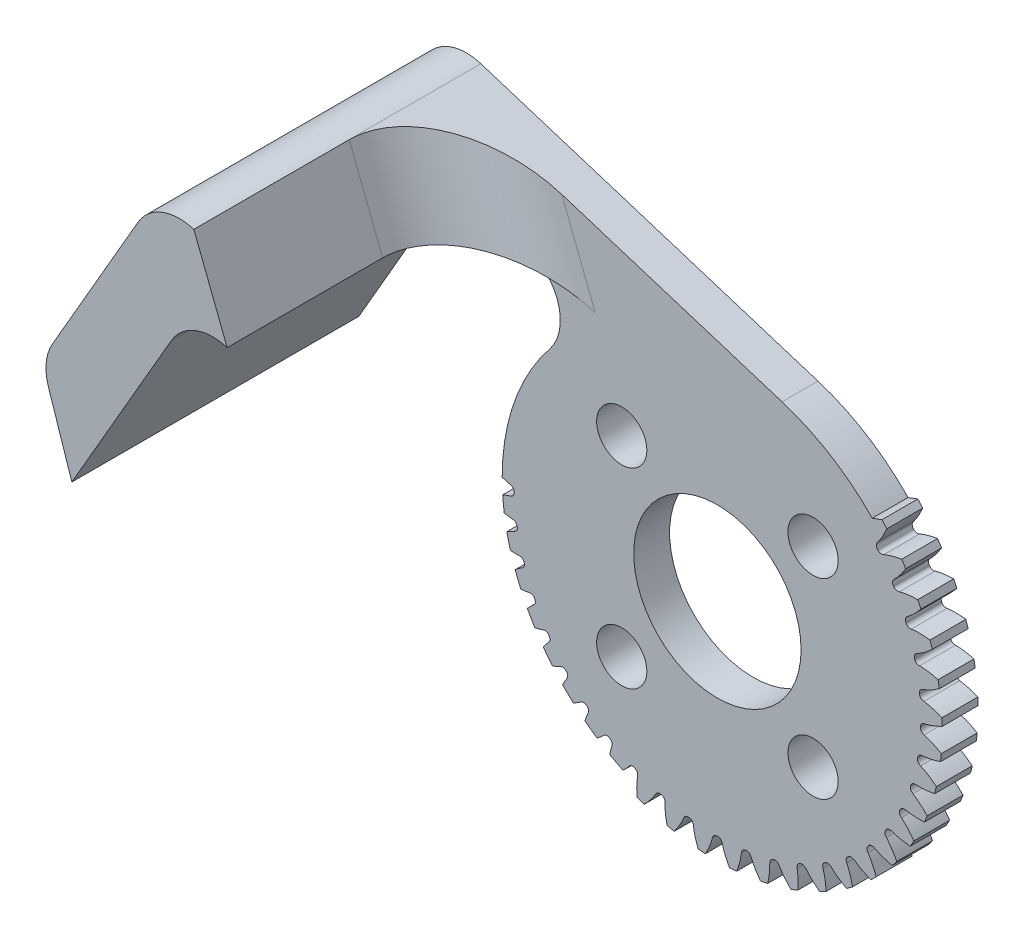
SolidWorks part; units mm, degrees
ref_plane "Front Plane" through (0, 0, 0) normal (0, 0, 1) x (1, 0, 0)
ref_plane "Top Plane" through (0, 0, 0) normal (0, 1, 0) x (1, 0, 0)
ref_plane "Right Plane" through (0, 0, 0) normal (1, 0, 0) x (0, 0, -1)
sketch "Sketch1" plane through (0, 0, 0) normal (0, 0, 1) x (-1, 0, 0)
  line L0 (-997.4582, 1.777) -> (0.6857, 1.777) construction
  line L3 (27.2085, 36.8505) -> (35.5323, 22.4334)
  line L11 (35.5323, 22.4334) -> (37.4944, 28.3526)
  line L14 (25.33, 45.8357) -> (-2.8709, 36.9439)
  line L15 (22.5416, 38.6653) -> (18.4787, 37.3843)
  line L17 (29.9969, 44.0208) -> (37.1617, 31.6112)
  line L18 (22.5416, 38.6653) -> (25.33, 45.8357)
  line L20 (-14.6013, 17.1719) -> (-14.584, 17.1703)
  line L21 (10.5418, 11.777) -> (-5.4582, 11.777) construction
  line L22 (10.5418, 11.777) -> (10.5418, 27.777) construction
  line L23 (10.5418, 27.777) -> (-5.4582, 27.777) construction
  line L24 (-5.4582, 11.777) -> (-5.4582, 27.777) construction
  line L25 (2.5418, 27.777) -> (2.5418, 11.777) construction
  line L26 (10.5418, 19.777) -> (-5.4582, 19.777) construction
  line L27 (-14.4428, 16.3692) -> (-14.4584, 16.3618)
  line L28 (-14.0719, 14.8114) -> (-14.0546, 14.8122)
  line L29 (-13.8032, 14.0386) -> (-13.8177, 14.0291)
  line L30 (-13.2191, 12.5475) -> (-13.2021, 12.5507)
  line L31 (-12.8455, 11.8196) -> (-12.8585, 11.8082)
  line L32 (-12.0596, 10.4244) -> (-12.0432, 10.4299)
  line L33 (-11.5883, 9.7556) -> (-11.5996, 9.7425)
  line L34 (-10.6158, 8.4833) -> (-10.6003, 8.491)
  line L35 (-10.0561, 7.8866) -> (-10.0654, 7.872)
  line L36 (-8.916, 6.762) -> (-8.9017, 6.7718)
  line L37 (-8.2786, 6.249) -> (-8.2859, 6.2333)
  line L38 (-6.9931, 5.2941) -> (-6.9804, 5.3058)
  line L39 (-6.2906, 4.8747) -> (-6.2956, 4.8582)
  line L40 (-4.8847, 4.108) -> (-4.8737, 4.1214)
  line L41 (-4.1307, 3.7905) -> (-4.1333, 3.7734)
  line L42 (-2.6317, 3.2269) -> (-2.6227, 3.2417)
  line L43 (-1.8408, 3.0175) -> (-1.841, 3.0002)
  line L44 (-0.278, 2.668) -> (-0.2712, 2.6838)
  line L45 (0.5343, 2.5706) -> (0.5365, 2.5535)
  line L46 (2.1305, 2.442) -> (2.1351, 2.4587)
  line L47 (2.9485, 2.4587) -> (2.9531, 2.442)
  line L48 (4.5471, 2.5535) -> (4.5493, 2.5706)
  line L49 (5.3548, 2.6838) -> (5.3617, 2.668)
  line L50 (6.9246, 3.0002) -> (6.9244, 3.0175)
  line L51 (7.7063, 3.2417) -> (7.7153, 3.2269)
  line L52 (9.2169, 3.7734) -> (9.2143, 3.7905)
  line L53 (9.9573, 4.1214) -> (9.9683, 4.108)
  line L54 (11.3792, 4.8582) -> (11.3742, 4.8747)
  line L55 (12.064, 5.3058) -> (12.0767, 5.2941)
  line L56 (13.3695, 6.2333) -> (13.3623, 6.249)
  line L57 (13.9854, 6.7718) -> (13.9996, 6.762)
  line L58 (15.149, 7.872) -> (15.1397, 7.8866)
  line L59 (15.684, 8.491) -> (15.6994, 8.4833)
  line L60 (16.6832, 9.7425) -> (16.6719, 9.7556)
  line L61 (17.1268, 10.4299) -> (17.1432, 10.4244)
  line L62 (17.9421, 11.8082) -> (17.9291, 11.8196)
  line L63 (18.2857, 12.5507) -> (18.3027, 12.5475)
  line L64 (18.9013, 14.0291) -> (18.8868, 14.0386)
  line L65 (19.1382, 14.8122) -> (19.1555, 14.8114)
  line L66 (19.542, 16.3618) -> (19.5264, 16.3692)
  line L67 (19.6676, 17.1703) -> (19.6849, 17.1719)
  line L68 (19.8519, 18.761) -> (19.8354, 18.7662)
  line L69 (19.8638, 19.5791) -> (19.8806, 19.5831)
  line L104 (-10.8652, 30.7736) -> (-10.8548, 30.7597)
  line L105 (-11.3556, 30.1188) -> (-11.3716, 30.1254)
  line L106 (-12.2651, 28.8007) -> (-12.253, 28.7884)
  line L107 (-12.6596, 28.084) -> (-12.6764, 28.0884)
  line L108 (-13.3769, 26.6522) -> (-13.3631, 26.6417)
  line L109 (-13.6678, 25.8875) -> (-13.685, 25.8895)
  line L110 (-14.1788, 24.3698) -> (-14.1637, 24.3613)
  line L111 (-14.3605, 23.5721) -> (-14.3778, 23.5717)
  line L112 (-14.6552, 21.9981) -> (-14.6391, 21.9918)
  line L113 (-14.7242, 21.1828) -> (-14.7412, 21.18)
  line L114 (-14.797, 19.5831) -> (-14.7802, 19.5791)
  line L115 (-14.7518, 18.7662) -> (-14.7683, 18.761)
  line L116 (10.5418, -16.223) -> (-5.4582, -16.223) construction
  line L117 (2.5418, -24.223) -> (2.5418, -8.223) construction
  line L118 (-5.4582, -8.223) -> (-5.4582, -24.223) construction
  line L119 (10.5418, -24.223) -> (-5.4582, -24.223) construction
  line L120 (10.5418, -8.223) -> (10.5418, -24.223) construction
  line L121 (10.5418, -8.223) -> (-5.4582, -8.223) construction
  line L122 (-14.7518, -15.2121) -> (-14.7683, -15.207)
  line L123 (-14.797, -16.029) -> (-14.7802, -16.025)
  line L124 (-14.7242, -17.6288) -> (-14.7412, -17.6259)
  line L125 (-14.6552, -18.444) -> (-14.6391, -18.4377)
  line L126 (-14.3605, -20.018) -> (-14.3778, -20.0176)
  line L127 (-14.1788, -20.8158) -> (-14.1637, -20.8073)
  line L128 (-13.6678, -22.3334) -> (-13.685, -22.3354)
  line L129 (-13.3769, -23.0981) -> (-13.3631, -23.0876)
  line L130 (-12.6596, -24.5299) -> (-12.6764, -24.5343)
  line L131 (-12.2651, -25.2467) -> (-12.253, -25.2343)
  line L132 (-11.3556, -26.5647) -> (-11.3716, -26.5714)
  line L133 (-10.8652, -27.2196) -> (-10.8548, -27.2057)
  line L134 (19.8638, -16.025) -> (19.8806, -16.029)
  line L135 (19.8519, -15.207) -> (19.8354, -15.2121)
  line L136 (19.6676, -13.6162) -> (19.6849, -13.6178)
  line L137 (19.542, -12.8077) -> (19.5264, -12.8152)
  line L138 (19.1382, -11.2581) -> (19.1555, -11.2573)
  line L139 (18.9013, -10.475) -> (18.8868, -10.4845)
  line L140 (18.2857, -8.9967) -> (18.3027, -8.9935)
  line L141 (17.9421, -8.2541) -> (17.9291, -8.2656)
  line L142 (17.1268, -6.8759) -> (17.1432, -6.8703)
  line L143 (16.6832, -6.1884) -> (16.6719, -6.2015)
  line L144 (15.684, -4.937) -> (15.6994, -4.9292)
  line L145 (15.149, -4.3179) -> (15.1397, -4.3325)
  line L146 (13.9854, -3.2178) -> (13.9996, -3.2079)
  line L147 (13.3695, -2.6792) -> (13.3623, -2.6949)
  line L148 (12.064, -1.7517) -> (12.0767, -1.74)
  line L149 (11.3792, -1.3041) -> (11.3742, -1.3207)
  line L150 (9.9573, -0.5673) -> (9.9683, -0.5539)
  line L151 (9.2169, -0.2194) -> (9.2143, -0.2365)
  line L152 (7.7063, 0.3124) -> (7.7153, 0.3271)
  line L153 (6.9246, 0.5539) -> (6.9244, 0.5366)
  line L154 (5.3548, 0.8702) -> (5.3617, 0.8861)
  line L155 (4.5471, 1.0006) -> (4.5493, 0.9834)
  line L156 (2.9485, 1.0954) -> (2.9531, 1.112)
  line L157 (2.1305, 1.112) -> (2.1351, 1.0954)
  line L158 (0.5343, 0.9834) -> (0.5365, 1.0006)
  line L159 (-0.278, 0.8861) -> (-0.2712, 0.8702)
  line L160 (-1.8408, 0.5366) -> (-1.841, 0.5539)
  line L161 (-2.6317, 0.3271) -> (-2.6227, 0.3124)
  line L162 (-4.1307, -0.2365) -> (-4.1333, -0.2194)
  line L163 (-4.8847, -0.5539) -> (-4.8737, -0.5673)
  line L164 (-6.2906, -1.3207) -> (-6.2956, -1.3041)
  line L165 (-6.9931, -1.74) -> (-6.9804, -1.7517)
  line L166 (-8.2786, -2.6949) -> (-8.2859, -2.6792)
  line L167 (-8.916, -3.2079) -> (-8.9017, -3.2178)
  line L168 (-10.0561, -4.3325) -> (-10.0654, -4.3179)
  line L169 (-10.6158, -4.9292) -> (-10.6003, -4.937)
  line L170 (-11.5883, -6.2015) -> (-11.5996, -6.1884)
  line L171 (-12.0596, -6.8703) -> (-12.0432, -6.8759)
  line L172 (-12.8455, -8.2656) -> (-12.8585, -8.2541)
  line L173 (-13.2191, -8.9935) -> (-13.2021, -8.9967)
  line L174 (-13.8032, -10.4845) -> (-13.8177, -10.475)
  line L175 (-14.0719, -11.2573) -> (-14.0546, -11.2581)
  line L176 (-14.4428, -12.8152) -> (-14.4584, -12.8077)
  line L177 (-14.6013, -13.6178) -> (-14.584, -13.6162)
  line L178 (22.5416, -35.1113) -> (25.33, -42.2816)
  line L179 (29.9969, -40.4668) -> (37.1617, -28.0571)
  line L180 (22.5416, -35.1113) -> (18.4787, -33.8302)
  line L181 (25.33, -42.2816) -> (-2.8709, -33.3899)
  line L182 (35.5323, -18.8793) -> (37.4944, -24.7985)
  line L183 (27.2085, -33.2964) -> (35.5323, -18.8793)
  arc A0 (-2.8709, 36.9439) -> (-10.4063, 32.2809) centre (2.5418, 19.777) ccw
  circle A2 centre (2.5418, 19.777) radius 7
  circle A4 centre (-5.4582, 27.777) radius 2.1
  circle A5 centre (10.5418, 27.777) radius 2.1
  circle A6 centre (10.5418, 11.777) radius 2.1
  circle A7 centre (-5.4582, 11.777) radius 2.1
  arc A12 (29.9969, 44.0208) -> (25.33, 45.8357) centre (26.5328, 42.0208) ccw
  arc A13 (37.4944, 28.3526) -> (37.1617, 31.6112) centre (33.6976, 29.6112) ccw
  arc A18 (18.4787, 37.3843) -> (16.5652, 31.0617) centre (19.6815, 33.5694) ccw
  arc A19 (27.2085, 36.8505) -> (22.5416, 38.6653) centre (23.7444, 34.8505) ccw
  arc A20 (-16.1848, 18.118) -> (-16.1206, 17.5063) centre (2.5418, 19.777) ccw
  arc A21 (-14.2083, 16.8729) -> (-14.1914, 16.7771) centre (2.5418, 19.777) ccw
  arc A22 (-15.7717, 15.5279) -> (-15.6229, 14.9311) centre (2.5418, 19.777) ccw
  arc A23 (-13.6411, 14.57) -> (-13.6111, 14.4775) centre (2.5418, 19.777) ccw
  arc A24 (-15.0021, 13.0205) -> (-14.7717, 12.4503) centre (2.5418, 19.777) ccw
  arc A25 (-12.7589, 12.3685) -> (-12.7163, 12.281) centre (2.5418, 19.777) ccw
  arc A26 (-13.891, 10.6446) -> (-13.5835, 10.112) centre (2.5418, 19.777) ccw
  arc A27 (-11.579, 10.3111) -> (-11.5246, 10.2305) centre (2.5418, 19.777) ccw
  arc A28 (-12.4601, 8.4465) -> (-12.0815, 7.9618) centre (2.5418, 19.777) ccw
  arc A29 (-10.1241, 8.438) -> (-10.0591, 8.3657) centre (2.5418, 19.777) ccw
  arc A30 (-10.7372, 6.4689) -> (-10.2948, 6.0416) centre (2.5418, 19.777) ccw
  arc A31 (-8.4228, 6.7856) -> (-8.3483, 6.7231) centre (2.5418, 19.777) ccw
  arc A32 (-8.7558, 4.7503) -> (-8.2583, 4.3888) centre (2.5418, 19.777) ccw
  arc A33 (-6.508, 5.386) -> (-6.4255, 5.3345) centre (2.5418, 19.777) ccw
  arc A34 (-6.5546, 3.3242) -> (-6.0116, 3.0355) centre (2.5418, 19.777) ccw
  arc A35 (-4.4171, 4.2666) -> (-4.3283, 4.227) centre (2.5418, 19.777) ccw
  arc A36 (-4.1763, 2.2183) -> (-3.5984, 2.008) centre (2.5418, 19.777) ccw
  arc A37 (-2.1907, 3.4491) -> (-2.0973, 3.4222) centre (2.5418, 19.777) ccw
  arc A39 (0.1277, 2.9493) -> (0.224, 2.9358) centre (2.5418, 19.777) ccw
  arc A41 (2.4932, 2.7771) -> (2.5904, 2.7771) centre (2.5418, 19.777) ccw
  arc A43 (4.8596, 2.9358) -> (4.9559, 2.9493) centre (2.5418, 19.777) ccw
  arc A45 (7.1809, 3.4222) -> (7.2744, 3.4491) centre (2.5418, 19.777) ccw
  arc A46 (8.682, 2.008) -> (9.2599, 2.2183) centre (2.5418, 19.777) ccw
  arc A47 (9.4119, 4.227) -> (9.5007, 4.2666) centre (2.5418, 19.777) ccw
  arc A49 (11.5092, 5.3345) -> (11.5916, 5.386) centre (2.5418, 19.777) ccw
  arc A51 (13.4319, 6.7231) -> (13.5064, 6.7856) centre (2.5418, 19.777) ccw
  arc A53 (15.1427, 8.3657) -> (15.2078, 8.438) centre (2.5418, 19.777) ccw
  arc A55 (16.6082, 10.2305) -> (16.6626, 10.3111) centre (2.5418, 19.777) ccw
  arc A57 (17.7999, 12.281) -> (17.8426, 12.3685) centre (2.5418, 19.777) ccw
  arc A59 (18.6947, 14.4775) -> (18.7247, 14.57) centre (2.5418, 19.777) ccw
  arc A61 (19.275, 16.7771) -> (19.2919, 16.8729) centre (2.5418, 19.777) ccw
  arc A63 (19.5297, 19.1351) -> (19.5331, 19.2323) centre (2.5418, 19.777) ccw
  arc A98 (-11.2217, 32.5835) -> (-11.6332, 32.1265) centre (2.5418, 19.777) ccw
  arc A99 (-10.8244, 30.2816) -> (-10.8843, 30.2049) centre (2.5418, 19.777) ccw
  arc A100 (-12.8701, 30.5434) -> (-13.214, 30.0335) centre (2.5418, 19.777) ccw
  arc A101 (-12.1563, 28.3191) -> (-12.2049, 28.2349) centre (2.5418, 19.777) ccw
  arc A102 (-14.2185, 28.2937) -> (-14.4881, 27.7409) centre (2.5418, 19.777) ccw
  arc A103 (-13.202, 26.1904) -> (-13.2385, 26.1002) centre (2.5418, 19.777) ccw
  arc A104 (-15.2406, 25.8782) -> (-15.4307, 25.2933) centre (2.5418, 19.777) ccw
  arc A105 (-13.9414, 23.9369) -> (-13.9649, 23.8425) centre (2.5418, 19.777) ccw
  arc A106 (-15.9167, 23.344) -> (-16.0235, 22.7384) centre (2.5418, 19.777) ccw
  arc A107 (-14.3599, 21.6024) -> (-14.3701, 21.5056) centre (2.5418, 19.777) ccw
  arc A108 (-16.2335, 20.7404) -> (-16.255, 20.1257) centre (2.5418, 19.777) ccw
  arc A109 (-14.4495, 19.2323) -> (-14.4461, 19.1351) centre (2.5418, 19.777) ccw
  arc A110 (10.4325, 3.5987) -> (11.5418, 4.1886) centre (2.5418, 19.777) ccw
  arc A111 (16.3306, -4.6528) -> (17.1041, -5.6428) centre (2.5418, -16.223) cw
  arc A112 (17.8067, -6.6844) -> (18.4349, -7.7725) centre (2.5418, -16.223) cw
  arc A113 (12.6073, 4.8544) -> (13.6237, 5.5928) centre (2.5418, 19.777) ccw
  arc A114 (14.5862, 6.4004) -> (15.4899, 7.2732) centre (2.5418, 19.777) ccw
  arc A115 (20.5418, 19.777) -> (16.5652, 31.0617) centre (2.5418, 19.777) ccw
  arc A116 (20.3666, 17.2719) -> (20.498, 18.5214) centre (2.5418, 19.777) ccw
  arc A117 (19.8445, 14.8156) -> (20.1485, 16.0346) centre (2.5418, 19.777) ccw
  arc A118 (18.9856, 12.4558) -> (19.4563, 13.6207) centre (2.5418, 19.777) ccw
  arc A119 (17.8067, 10.2385) -> (18.4349, 11.3265) centre (2.5418, 19.777) ccw
  arc A120 (16.3306, 8.2069) -> (17.1041, 9.1969) centre (2.5418, 19.777) ccw
  arc A121 (18.9856, -8.9017) -> (19.4563, -10.0666) centre (2.5418, -16.223) cw
  arc A122 (19.8445, -11.2615) -> (20.1485, -12.4806) centre (2.5418, -16.223) cw
  arc A123 (20.3666, -13.7179) -> (20.498, -14.9674) centre (2.5418, -16.223) cw
  arc A124 (20.5418, -16.223) -> (16.5652, -27.5077) centre (2.5418, -16.223) cw
  arc A125 (14.5862, -2.8464) -> (15.4899, -3.7191) centre (2.5418, -16.223) cw
  arc A126 (12.6073, -1.3003) -> (13.6237, -2.0388) centre (2.5418, -16.223) cw
  arc A127 (10.4325, -0.0447) -> (11.5418, -0.6345) centre (2.5418, -16.223) cw
  arc A128 (-14.4495, -15.6783) -> (-14.4461, -15.5811) centre (2.5418, -16.223) cw
  arc A129 (-16.2335, -17.1863) -> (-16.255, -16.5717) centre (2.5418, -16.223) cw
  arc A130 (-14.3599, -18.0483) -> (-14.3701, -17.9516) centre (2.5418, -16.223) cw
  arc A131 (-15.9167, -19.7899) -> (-16.0235, -19.1843) centre (2.5418, -16.223) cw
  arc A132 (-13.9414, -20.3828) -> (-13.9649, -20.2884) centre (2.5418, -16.223) cw
  arc A133 (-15.2406, -22.3242) -> (-15.4307, -21.7393) centre (2.5418, -16.223) cw
  arc A134 (-13.202, -22.6363) -> (-13.2385, -22.5462) centre (2.5418, -16.223) cw
  arc A135 (-14.2185, -24.7396) -> (-14.4881, -24.1869) centre (2.5418, -16.223) cw
  arc A136 (-12.1563, -24.765) -> (-12.2049, -24.6808) centre (2.5418, -16.223) cw
  arc A137 (-12.8701, -26.9893) -> (-13.214, -26.4795) centre (2.5418, -16.223) cw
  arc A138 (-10.8244, -26.7275) -> (-10.8843, -26.6509) centre (2.5418, -16.223) cw
  arc A139 (-11.2217, -29.0295) -> (-11.6332, -28.5724) centre (2.5418, -16.223) cw
  arc A140 (19.5297, -15.5811) -> (19.5331, -15.6783) centre (2.5418, -16.223) cw
  arc A141 (19.275, -13.2231) -> (19.2919, -13.3188) centre (2.5418, -16.223) cw
  arc A142 (18.6947, -10.9235) -> (18.7247, -11.0159) centre (2.5418, -16.223) cw
  arc A143 (17.7999, -8.727) -> (17.8426, -8.8144) centre (2.5418, -16.223) cw
  arc A144 (16.6082, -6.6764) -> (16.6626, -6.757) centre (2.5418, -16.223) cw
  arc A145 (15.1427, -4.8117) -> (15.2078, -4.8839) centre (2.5418, -16.223) cw
  arc A146 (13.4319, -3.169) -> (13.5064, -3.2315) centre (2.5418, -16.223) cw
  arc A147 (11.5092, -1.7804) -> (11.5916, -1.832) centre (2.5418, -16.223) cw
  arc A148 (9.4119, -0.673) -> (9.5007, -0.7125) centre (2.5418, -16.223) cw
  arc A149 (8.682, 1.5461) -> (9.2599, 1.3357) centre (2.5418, -16.223) cw
  arc A150 (7.1809, 0.1318) -> (7.2744, 0.105) centre (2.5418, -16.223) cw
  arc A151 (6.1492, 2.2277) -> (6.7508, 2.0998) centre (2.5418, -16.223) cw
  arc A152 (4.8596, 0.6183) -> (4.9559, 0.6048) centre (2.5418, -16.223) cw
  arc A153 (3.5463, 2.5502) -> (4.1598, 2.5073) centre (2.5418, -16.223) cw
  arc A154 (2.4932, 0.777) -> (2.5904, 0.777) centre (2.5418, -16.223) cw
  arc A155 (0.9238, 2.5073) -> (1.5373, 2.5502) centre (2.5418, -16.223) cw
  arc A156 (0.1277, 0.6048) -> (0.224, 0.6183) centre (2.5418, -16.223) cw
  arc A157 (-1.6672, 2.0998) -> (-1.0656, 2.2277) centre (2.5418, -16.223) cw
  arc A158 (-2.1907, 0.105) -> (-2.0973, 0.1318) centre (2.5418, -16.223) cw
  arc A159 (-4.1763, 1.3357) -> (-3.5984, 1.5461) centre (2.5418, -16.223) cw
  arc A160 (-4.4171, -0.7125) -> (-4.3283, -0.673) centre (2.5418, -16.223) cw
  arc A161 (-6.5546, 0.2299) -> (-6.0116, 0.5186) centre (2.5418, -16.223) cw
  arc A162 (-6.508, -1.832) -> (-6.4255, -1.7804) centre (2.5418, -16.223) cw
  arc A163 (-8.7558, -1.1962) -> (-8.2583, -0.8347) centre (2.5418, -16.223) cw
  arc A164 (-8.4228, -3.2315) -> (-8.3483, -3.169) centre (2.5418, -16.223) cw
  arc A165 (-10.7372, -2.9148) -> (-10.2948, -2.4876) centre (2.5418, -16.223) cw
  arc A166 (-10.1241, -4.8839) -> (-10.0591, -4.8117) centre (2.5418, -16.223) cw
  arc A167 (-12.4601, -4.8924) -> (-12.0815, -4.4078) centre (2.5418, -16.223) cw
  arc A168 (-11.579, -6.757) -> (-11.5246, -6.6764) centre (2.5418, -16.223) cw
  arc A169 (-13.891, -7.0905) -> (-13.5835, -6.5579) centre (2.5418, -16.223) cw
  arc A170 (-12.7589, -8.8144) -> (-12.7163, -8.727) centre (2.5418, -16.223) cw
  arc A171 (-15.0021, -9.4664) -> (-14.7717, -8.8962) centre (2.5418, -16.223) cw
  arc A172 (-13.6411, -11.0159) -> (-13.6111, -10.9235) centre (2.5418, -16.223) cw
  arc A173 (-15.7717, -11.9738) -> (-15.6229, -11.3771) centre (2.5418, -16.223) cw
  arc A174 (-14.2083, -13.3188) -> (-14.1914, -13.2231) centre (2.5418, -16.223) cw
  arc A175 (-16.1848, -14.5639) -> (-16.1206, -13.9523) centre (2.5418, -16.223) cw
  arc A176 (27.2085, -33.2964) -> (22.5416, -35.1113) centre (23.7444, -31.2964) cw
  arc A177 (18.4787, -33.8302) -> (16.5652, -27.5077) centre (19.6815, -30.0154) cw
  arc A178 (37.4944, -24.7985) -> (37.1617, -28.0571) centre (33.6976, -26.0571) cw
  arc A179 (29.9969, -40.4668) -> (25.33, -42.2816) centre (26.5328, -38.4668) cw
  circle A180 centre (-5.4582, -8.223) radius 2.1
  circle A181 centre (10.5418, -8.223) radius 2.1
  circle A182 centre (10.5418, -24.223) radius 2.1
  circle A183 centre (-5.4582, -24.223) radius 2.1
  circle A184 centre (2.5418, -16.223) radius 7
  arc A185 (-2.8709, -33.3899) -> (-10.4063, -28.7268) centre (2.5418, -16.223) cw
  spline S0 degree 3 poles (-14.7683, 18.761) (-14.8625, 18.7338) (-15.0114, 18.6848) (-15.2184, 18.6056) (-15.3979, 18.53) (-15.5921, 18.4404) (-15.8001, 18.3357) (-15.9995, 18.227) (-16.1287, 18.1517) (-16.1848, 18.118) knots 0 0 0 0 0.131774 0.210453 0.29766 0.393396 0.49766 0.610453 0.698458 0.698458 0.698458 0.698458 weights 1 1 1 1 1 1 1 1 1 1
  spline S1 degree 3 poles (-16.1206, 17.5063) (-16.0586, 17.4851) (-15.9166, 17.4382) (-15.699, 17.3733) (-15.4737, 17.3143) (-15.2652, 17.267) (-15.0739, 17.2303) (-14.8549, 17.1959) (-14.6991, 17.1789) (-14.6013, 17.1719) knots 0.301542 0.301542 0.301542 0.301542 0.389547 0.50234 0.606604 0.70234 0.789547 0.868226 1 1 1 1 weights 1 1 1 1 1 1 1 1 1 1
  spline S2 degree 3 poles (-14.584, 17.1703) (-14.5667, 17.1689) (-14.5374, 17.165) (-14.496, 17.1567) (-14.4585, 17.1463) (-14.4182, 17.1314) (-14.3741, 17.1095) (-14.326, 17.0767) (-14.254, 17.0064) (-14.218, 16.9305) (-14.2083, 16.8729) knots 0 0 0 0 0.101113 0.170973 0.245147 0.32664 0.419682 0.529844 0.663118 1 1 1 1 weights 1 1 1 1 1 1 1 1 1 1 1
  spline S3 degree 3 poles (-14.1914, 16.7771) (-14.1809, 16.7197) (-14.1887, 16.6361) (-14.2323, 16.5453) (-14.2663, 16.4981) (-14.3002, 16.4624) (-14.333, 16.4347) (-14.3647, 16.4121) (-14.4008, 16.3901) (-14.4269, 16.3764) (-14.4428, 16.3692) knots 0 0 0 0 0.336882 0.470156 0.580318 0.67336 0.754853 0.829027 0.898887 1 1 1 1 weights 1 1 1 1 1 1 1 1 1 1 1
  spline S4 degree 3 poles (-14.4584, 16.3618) (-14.548, 16.3218) (-14.6886, 16.2525) (-14.8825, 16.1453) (-15.0498, 16.0454) (-15.2296, 15.9296) (-15.421, 15.7971) (-15.6034, 15.6616) (-15.7207, 15.5691) (-15.7717, 15.5279) knots 0 0 0 0 0.131774 0.210453 0.29766 0.393396 0.49766 0.610453 0.698458 0.698458 0.698458 0.698458 weights 1 1 1 1 1 1 1 1 1 1
  spline S5 degree 3 poles (-15.6229, 14.9311) (-15.5586, 14.9187) (-15.4115, 14.8921) (-15.1869, 14.8581) (-14.9556, 14.8309) (-14.7425, 14.8132) (-14.548, 14.8035) (-14.3264, 14.7998) (-14.1697, 14.8047) (-14.0719, 14.8114) knots 0.301542 0.301542 0.301542 0.301542 0.389547 0.50234 0.606604 0.70234 0.789547 0.868226 1 1 1 1 weights 1 1 1 1 1 1 1 1 1 1
  spline S6 degree 3 poles (-14.0546, 14.8122) (-14.0372, 14.8133) (-14.0077, 14.8135) (-13.9655, 14.811) (-13.9269, 14.806) (-13.8849, 14.7968) (-13.8383, 14.7812) (-13.7861, 14.7555) (-13.705, 14.6958) (-13.6588, 14.6257) (-13.6411, 14.57) knots 0 0 0 0 0.101113 0.170973 0.245147 0.32664 0.419682 0.529844 0.663118 1 1 1 1 weights 1 1 1 1 1 1 1 1 1 1 1
  spline S7 degree 3 poles (-13.6111, 14.4775) (-13.5926, 14.4221) (-13.5888, 14.3382) (-13.6193, 14.2423) (-13.6464, 14.1907) (-13.675, 14.1507) (-13.7036, 14.1187) (-13.7318, 14.0919) (-13.7645, 14.0651) (-13.7885, 14.0479) (-13.8032, 14.0386) knots 0 0 0 0 0.336882 0.470156 0.580318 0.67336 0.754853 0.829027 0.898887 1 1 1 1 weights 1 1 1 1 1 1 1 1 1 1 1
  spline S8 degree 3 poles (-13.8177, 14.0291) (-13.9008, 13.9769) (-14.0304, 13.8888) (-14.2075, 13.7556) (-14.3592, 13.6334) (-14.5212, 13.4938) (-14.6923, 13.3359) (-14.854, 13.1763) (-14.9574, 13.0683) (-15.0021, 13.0205) knots 0 0 0 0 0.131774 0.210453 0.29766 0.393396 0.49766 0.610453 0.698458 0.698458 0.698458 0.698458 weights 1 1 1 1 1 1 1 1 1 1
  spline S9 degree 3 poles (-14.7717, 12.4503) (-14.7063, 12.4469) (-14.5569, 12.441) (-14.3298, 12.4386) (-14.097, 12.4439) (-13.8835, 12.456) (-13.6895, 12.4734) (-13.4696, 12.5007) (-13.3151, 12.5273) (-13.2191, 12.5475) knots 0.301542 0.301542 0.301542 0.301542 0.389547 0.50234 0.606604 0.70234 0.789547 0.868226 1 1 1 1 weights 1 1 1 1 1 1 1 1 1 1
  spline S10 degree 3 poles (-13.2021, 12.5507) (-13.185, 12.5543) (-13.1558, 12.5585) (-13.1137, 12.562) (-13.0748, 12.5623) (-13.032, 12.5591) (-12.9836, 12.5502) (-12.9283, 12.5319) (-12.8397, 12.4841) (-12.7842, 12.4211) (-12.7589, 12.3685) knots 0 0 0 0 0.101113 0.170973 0.245147 0.32664 0.419682 0.529844 0.663118 1 1 1 1 weights 1 1 1 1 1 1 1 1 1 1 1
  spline S11 degree 3 poles (-12.7163, 12.281) (-12.6904, 12.2288) (-12.6749, 12.1462) (-12.6918, 12.0469) (-12.7114, 11.9921) (-12.7342, 11.9485) (-12.758, 11.9128) (-12.7822, 11.8824) (-12.8109, 11.8513) (-12.8322, 11.8309) (-12.8455, 11.8196) knots 0 0 0 0 0.336882 0.470156 0.580318 0.67336 0.754853 0.829027 0.898887 1 1 1 1 weights 1 1 1 1 1 1 1 1 1 1 1
  spline S12 degree 3 poles (-12.8585, 11.8082) (-12.9335, 11.745) (-13.0496, 11.6397) (-13.2065, 11.4831) (-13.3397, 11.341) (-13.4806, 11.1802) (-13.6282, 11) (-13.7661, 10.8196) (-13.8534, 10.6982) (-13.891, 10.6446) knots 0 0 0 0 0.131774 0.210453 0.29766 0.393396 0.49766 0.610453 0.698458 0.698458 0.698458 0.698458 weights 1 1 1 1 1 1 1 1 1 1
  spline S13 degree 3 poles (-13.5835, 10.112) (-13.5183, 10.1178) (-13.3695, 10.1327) (-13.1443, 10.1619) (-12.9145, 10.1996) (-12.7047, 10.2412) (-12.5151, 10.2855) (-12.3011, 10.3431) (-12.1518, 10.391) (-12.0596, 10.4244) knots 0.301542 0.301542 0.301542 0.301542 0.389547 0.50234 0.606604 0.70234 0.789547 0.868226 1 1 1 1 weights 1 1 1 1 1 1 1 1 1 1
  spline S14 degree 3 poles (-12.0432, 10.4299) (-12.0267, 10.4358) (-11.9984, 10.4441) (-11.9572, 10.4533) (-11.9187, 10.4591) (-11.8759, 10.4619) (-11.8267, 10.4598) (-11.7694, 10.4494) (-11.675, 10.4144) (-11.6113, 10.3597) (-11.579, 10.3111) knots 0 0 0 0 0.101113 0.170973 0.245147 0.32664 0.419682 0.529844 0.663118 1 1 1 1 weights 1 1 1 1 1 1 1 1 1 1 1
  spline S15 degree 3 poles (-11.5246, 10.2305) (-11.4916, 10.1823) (-11.4648, 10.1027) (-11.4677, 10.0021) (-11.4795, 9.9451) (-11.496, 9.8987) (-11.5146, 9.86) (-11.5344, 9.8265) (-11.5584, 9.7917) (-11.5767, 9.7686) (-11.5883, 9.7556) knots 0 0 0 0 0.336882 0.470156 0.580318 0.67336 0.754853 0.829027 0.898887 1 1 1 1 weights 1 1 1 1 1 1 1 1 1 1 1
  spline S16 degree 3 poles (-11.5996, 9.7425) (-11.6651, 9.6694) (-11.7654, 9.549) (-11.8989, 9.3721) (-12.0111, 9.2128) (-12.1283, 9.034) (-12.2493, 8.835) (-12.3607, 8.6371) (-12.4303, 8.5048) (-12.4601, 8.4465) knots 0 0 0 0 0.131774 0.210453 0.29766 0.393396 0.49766 0.610453 0.698458 0.698458 0.698458 0.698458 weights 1 1 1 1 1 1 1 1 1 1
  spline S17 degree 3 poles (-12.0815, 7.9618) (-12.0177, 7.9766) (-11.8725, 8.0121) (-11.6535, 8.0724) (-11.4311, 8.1417) (-11.2292, 8.2121) (-11.0476, 8.2824) (-10.8437, 8.3692) (-10.7025, 8.4374) (-10.6158, 8.4833) knots 0.301542 0.301542 0.301542 0.301542 0.389547 0.50234 0.606604 0.70234 0.789547 0.868226 1 1 1 1 weights 1 1 1 1 1 1 1 1 1 1
  spline S18 degree 3 poles (-10.6003, 8.491) (-10.5849, 8.4991) (-10.558, 8.5113) (-10.5185, 8.5262) (-10.4812, 8.5373) (-10.4391, 8.546) (-10.3902, 8.5508) (-10.332, 8.5485) (-10.2336, 8.5269) (-10.1629, 8.4817) (-10.1241, 8.438) knots 0 0 0 0 0.101113 0.170973 0.245147 0.32664 0.419682 0.529844 0.663118 1 1 1 1 weights 1 1 1 1 1 1 1 1 1 1 1
  spline S19 degree 3 poles (-10.0591, 8.3657) (-10.0197, 8.3226) (-9.9821, 8.2475) (-9.9709, 8.1475) (-9.9747, 8.0894) (-9.9846, 8.0412) (-9.9976, 8.0003) (-10.0125, 7.9643) (-10.0315, 7.9265) (-10.0464, 7.9011) (-10.0561, 7.8866) knots 0 0 0 0 0.336882 0.470156 0.580318 0.67336 0.754853 0.829027 0.898887 1 1 1 1 weights 1 1 1 1 1 1 1 1 1 1 1
  spline S20 degree 3 poles (-10.0654, 7.872) (-10.1201, 7.7906) (-10.2027, 7.6573) (-10.3103, 7.4636) (-10.3992, 7.2903) (-10.4903, 7.0968) (-10.5825, 6.883) (-10.6653, 6.6715) (-10.7158, 6.5308) (-10.7372, 6.4689) knots 0 0 0 0 0.131774 0.210453 0.29766 0.393396 0.49766 0.610453 0.698458 0.698458 0.698458 0.698458 weights 1 1 1 1 1 1 1 1 1 1
  spline S21 degree 3 poles (-10.2948, 6.0416) (-10.2337, 6.0652) (-10.0948, 6.1206) (-9.8864, 6.2107) (-9.6758, 6.3103) (-9.4857, 6.4081) (-9.3156, 6.503) (-9.1257, 6.6174) (-8.9954, 6.7045) (-8.916, 6.762) knots 0.301542 0.301542 0.301542 0.301542 0.389547 0.50234 0.606604 0.70234 0.789547 0.868226 1 1 1 1 weights 1 1 1 1 1 1 1 1 1 1
  spline S22 degree 3 poles (-8.9017, 6.7718) (-8.8876, 6.782) (-8.8627, 6.7978) (-8.8256, 6.8181) (-8.7902, 6.8342) (-8.7497, 6.8487) (-8.7019, 6.8602) (-8.644, 6.866) (-8.5436, 6.8584) (-8.4672, 6.8234) (-8.4228, 6.7856) knots 0 0 0 0 0.101113 0.170973 0.245147 0.32664 0.419682 0.529844 0.663118 1 1 1 1 weights 1 1 1 1 1 1 1 1 1 1 1
  spline S23 degree 3 poles (-8.3483, 6.7231) (-8.3033, 6.6859) (-8.2556, 6.6167) (-8.2306, 6.5192) (-8.2263, 6.4611) (-8.2294, 6.412) (-8.2366, 6.3697) (-8.2464, 6.3321) (-8.2599, 6.292) (-8.2711, 6.2647) (-8.2786, 6.249) knots 0 0 0 0 0.336882 0.470156 0.580318 0.67336 0.754853 0.829027 0.898887 1 1 1 1 weights 1 1 1 1 1 1 1 1 1 1 1
  spline S24 degree 3 poles (-8.2859, 6.2333) (-8.3287, 6.145) (-8.3919, 6.0016) (-8.4716, 5.7948) (-8.5354, 5.6108) (-8.5988, 5.4065) (-8.6603, 5.1819) (-8.7129, 4.961) (-8.7433, 4.8146) (-8.7558, 4.7503) knots 0 0 0 0 0.131774 0.210453 0.29766 0.393396 0.49766 0.610453 0.698458 0.698458 0.698458 0.698458 weights 1 1 1 1 1 1 1 1 1 1
  spline S25 degree 3 poles (-8.2583, 4.3888) (-8.201, 4.4206) (-8.0712, 4.4948) (-7.8774, 4.6131) (-7.6827, 4.741) (-7.5081, 4.8643) (-7.3528, 4.9819) (-7.1807, 5.1216) (-7.0638, 5.226) (-6.9931, 5.2941) knots 0.301542 0.301542 0.301542 0.301542 0.389547 0.50234 0.606604 0.70234 0.789547 0.868226 1 1 1 1 weights 1 1 1 1 1 1 1 1 1 1
  spline S26 degree 3 poles (-6.9804, 5.3058) (-6.9678, 5.3178) (-6.9453, 5.3369) (-6.9114, 5.3622) (-6.8786, 5.3831) (-6.8406, 5.403) (-6.7948, 5.4211) (-6.7383, 5.4349) (-6.6378, 5.4414) (-6.5573, 5.4173) (-6.508, 5.386) knots 0 0 0 0 0.101113 0.170973 0.245147 0.32664 0.419682 0.529844 0.663118 1 1 1 1 weights 1 1 1 1 1 1 1 1 1 1 1
  spline S27 degree 3 poles (-6.4255, 5.3345) (-6.3758, 5.3039) (-6.3189, 5.2421) (-6.2807, 5.149) (-6.2683, 5.0921) (-6.2645, 5.0431) (-6.2657, 5.0001) (-6.2702, 4.9615) (-6.278, 4.9199) (-6.2853, 4.8914) (-6.2906, 4.8747) knots 0 0 0 0 0.336882 0.470156 0.580318 0.67336 0.754853 0.829027 0.898887 1 1 1 1 weights 1 1 1 1 1 1 1 1 1 1 1
  spline S28 degree 3 poles (-6.2956, 4.8582) (-6.3257, 4.7648) (-6.3683, 4.614) (-6.4184, 4.3981) (-6.4561, 4.207) (-6.4904, 3.9959) (-6.52, 3.7649) (-6.5413, 3.5388) (-6.5511, 3.3896) (-6.5546, 3.3242) knots 0 0 0 0 0.131774 0.210453 0.29766 0.393396 0.49766 0.610453 0.698458 0.698458 0.698458 0.698458 weights 1 1 1 1 1 1 1 1 1 1
  spline S29 degree 3 poles (-6.0116, 3.0355) (-5.9593, 3.075) (-5.8411, 3.1665) (-5.6655, 3.3106) (-5.4906, 3.4643) (-5.3348, 3.6108) (-5.1974, 3.7489) (-5.0465, 3.9111) (-4.9452, 4.0308) (-4.8847, 4.108) knots 0.301542 0.301542 0.301542 0.301542 0.389547 0.50234 0.606604 0.70234 0.789547 0.868226 1 1 1 1 weights 1 1 1 1 1 1 1 1 1 1
  spline S30 degree 3 poles (-4.8737, 4.1214) (-4.8629, 4.1351) (-4.8433, 4.1571) (-4.8132, 4.1868) (-4.7837, 4.2121) (-4.7488, 4.2372) (-4.706, 4.2614) (-4.6519, 4.283) (-4.5533, 4.3033) (-4.4703, 4.2907) (-4.4171, 4.2666) knots 0 0 0 0 0.101113 0.170973 0.245147 0.32664 0.419682 0.529844 0.663118 1 1 1 1 weights 1 1 1 1 1 1 1 1 1 1 1
  spline S31 degree 3 poles (-4.3283, 4.227) (-4.2748, 4.2037) (-4.2098, 4.1504) (-4.159, 4.0635) (-4.1388, 4.0089) (-4.1282, 3.9608) (-4.1235, 3.9182) (-4.1225, 3.8793) (-4.1244, 3.837) (-4.1277, 3.8077) (-4.1307, 3.7905) knots 0 0 0 0 0.336882 0.470156 0.580318 0.67336 0.754853 0.829027 0.898887 1 1 1 1 weights 1 1 1 1 1 1 1 1 1 1 1
  spline S32 degree 3 poles (-4.1333, 3.7734) (-4.1501, 3.6768) (-4.1713, 3.5215) (-4.1909, 3.3007) (-4.2016, 3.1062) (-4.2062, 2.8925) (-4.2034, 2.6596) (-4.193, 2.4327) (-4.1819, 2.2836) (-4.1763, 2.2183) knots 0 0 0 0 0.131774 0.210453 0.29766 0.393396 0.49766 0.610453 0.698458 0.698458 0.698458 0.698458 weights 1 1 1 1 1 1 1 1 1 1
  spline S33 degree 3 poles (-3.5984, 2.008) (-3.5521, 2.0544) (-3.4477, 2.1614) (-3.294, 2.3286) (-3.1421, 2.5052) (-3.0082, 2.6719) (-2.8914, 2.8278) (-2.7645, 3.0094) (-2.6809, 3.142) (-2.6317, 3.2269) knots 0.301542 0.301542 0.301542 0.301542 0.389547 0.50234 0.606604 0.70234 0.789547 0.868226 1 1 1 1 weights 1 1 1 1 1 1 1 1 1 1
  spline S34 degree 3 poles (-2.6227, 3.2417) (-2.6139, 3.2567) (-2.5976, 3.2813) (-2.5719, 3.3149) (-2.5462, 3.3441) (-2.5151, 3.3737) (-2.4761, 3.4037) (-2.4256, 3.4326) (-2.3307, 3.4664) (-2.2468, 3.4655) (-2.1907, 3.4491) knots 0 0 0 0 0.101113 0.170973 0.245147 0.32664 0.419682 0.529844 0.663118 1 1 1 1 weights 1 1 1 1 1 1 1 1 1 1 1
  spline S35 degree 3 poles (-2.0973, 3.4222) (-2.041, 3.4065) (-1.9693, 3.3628) (-1.9069, 3.2839) (-1.8793, 3.2326) (-1.8621, 3.1865) (-1.8515, 3.1449) (-1.8451, 3.1065) (-1.8411, 3.0644) (-1.8403, 3.0349) (-1.8408, 3.0175) knots 0 0 0 0 0.336882 0.470156 0.580318 0.67336 0.754853 0.829027 0.898887 1 1 1 1 weights 1 1 1 1 1 1 1 1 1 1 1
  spline S36 degree 3 poles (-1.841, 3.0002) (-1.8443, 2.9021) (-1.8437, 2.7454) (-1.8323, 2.5241) (-1.8158, 2.33) (-1.7906, 2.1176) (-1.7621, 1.9313) (-1.7416, 1.8159) (-1.7344, 1.777) knots 0 0 0 0 0.131774 0.210453 0.29766 0.393396 0.49766 0.550817 0.550817 0.550817 0.550817 weights 1 1 1 1 1 1 1 1 1
  spline S37 degree 3 poles (-0.751, 1.777) (-0.7272, 1.8139) (-0.6658, 1.9112) (-0.5737, 2.0659) (-0.4797, 2.2366) (-0.3793, 2.4341) (-0.3149, 2.5771) (-0.278, 2.668) knots 0.547707 0.547707 0.547707 0.547707 0.606604 0.70234 0.789547 0.868226 1 1 1 1 weights 1 1 1 1 1 1 1 1
  spline S38 degree 3 poles (-0.2712, 2.6838) (-0.2646, 2.7) (-0.2518, 2.7266) (-0.2311, 2.7634) (-0.2096, 2.7959) (-0.183, 2.8296) (-0.1486, 2.8647) (-0.1025, 2.9003) (-0.0133, 2.9471) (0.07, 2.9578) (0.1277, 2.9493) knots 0 0 0 0 0.101113 0.170973 0.245147 0.32664 0.419682 0.529844 0.663118 1 1 1 1 weights 1 1 1 1 1 1 1 1 1 1 1
  spline S39 degree 3 poles (0.224, 2.9358) (0.2819, 2.9281) (0.359, 2.8947) (0.4318, 2.8252) (0.4663, 2.7783) (0.4897, 2.735) (0.506, 2.6953) (0.5177, 2.6582) (0.5275, 2.6171) (0.5324, 2.588) (0.5343, 2.5706) knots 0 0 0 0 0.336882 0.470156 0.580318 0.67336 0.754853 0.829027 0.898887 1 1 1 1 weights 1 1 1 1 1 1 1 1 1 1 1
  spline S40 degree 3 poles (0.5365, 2.5535) (0.5469, 2.4559) (0.5694, 2.3008) (0.6114, 2.0832) (0.6483, 1.9216) (0.6749, 1.8178) (0.6857, 1.777) knots 0 0 0 0 0.131774 0.210453 0.29766 0.35438 0.35438 0.35438 0.35438 weights 1 1 1 1 1 1 1
  spline S41 degree 3 poles (1.9092, 1.777) (1.9382, 1.8485) (1.9869, 1.9752) (2.0628, 2.1964) (2.1066, 2.3469) (2.1305, 2.442) knots 0.685922 0.685922 0.685922 0.685922 0.789547 0.868226 1 1 1 1 weights 1 1 1 1 1 1
  spline S42 degree 3 poles (2.1351, 2.4587) (2.1394, 2.4756) (2.1483, 2.5037) (2.1638, 2.5431) (2.1805, 2.5782) (2.2021, 2.6153) (2.2314, 2.6549) (2.272, 2.6965) (2.3538, 2.7552) (2.4348, 2.7775) (2.4932, 2.7771) knots 0 0 0 0 0.101113 0.170973 0.245147 0.32664 0.419682 0.529844 0.663118 1 1 1 1 weights 1 1 1 1 1 1 1 1 1 1 1
  spline S43 degree 3 poles (2.5904, 2.7771) (2.6488, 2.7775) (2.7298, 2.7552) (2.8116, 2.6965) (2.8523, 2.6549) (2.8815, 2.6153) (2.9031, 2.5782) (2.9199, 2.5431) (2.9353, 2.5037) (2.9442, 2.4756) (2.9485, 2.4587) knots 0 0 0 0 0.336882 0.470156 0.580318 0.67336 0.754853 0.829027 0.898887 1 1 1 1 weights 1 1 1 1 1 1 1 1 1 1 1
  spline S44 degree 3 poles (2.9531, 2.442) (2.977, 2.3469) (3.0208, 2.1964) (3.0967, 1.9752) (3.1454, 1.8485) (3.1744, 1.777) knots 0 0 0 0 0.131774 0.210453 0.314078 0.314078 0.314078 0.314078 weights 1 1 1 1 1 1
  spline S45 degree 3 poles (4.3979, 1.777) (4.4088, 1.8178) (4.4353, 1.9216) (4.4722, 2.0832) (4.5142, 2.3008) (4.5367, 2.4559) (4.5471, 2.5535) knots 0.64562 0.64562 0.64562 0.64562 0.70234 0.789547 0.868226 1 1 1 1 weights 1 1 1 1 1 1 1
  spline S46 degree 3 poles (4.5493, 2.5706) (4.5512, 2.588) (4.5562, 2.6171) (4.5659, 2.6582) (4.5776, 2.6953) (4.5939, 2.735) (4.6173, 2.7783) (4.6518, 2.8252) (4.7246, 2.8947) (4.8017, 2.9281) (4.8596, 2.9358) knots 0 0 0 0 0.101113 0.170973 0.245147 0.32664 0.419682 0.529844 0.663118 1 1 1 1 weights 1 1 1 1 1 1 1 1 1 1 1
  spline S47 degree 3 poles (4.9559, 2.9493) (5.0136, 2.9578) (5.0969, 2.9471) (5.1861, 2.9003) (5.2322, 2.8647) (5.2666, 2.8296) (5.2932, 2.7959) (5.3147, 2.7634) (5.3354, 2.7266) (5.3482, 2.7) (5.3548, 2.6838) knots 0 0 0 0 0.336882 0.470156 0.580318 0.67336 0.754853 0.829027 0.898887 1 1 1 1 weights 1 1 1 1 1 1 1 1 1 1 1
  spline S48 degree 3 poles (5.3617, 2.668) (5.3986, 2.5771) (5.4629, 2.4341) (5.5633, 2.2366) (5.6573, 2.0659) (5.7494, 1.9112) (5.8108, 1.8139) (5.8346, 1.777) knots 0 0 0 0 0.131774 0.210453 0.29766 0.393396 0.452293 0.452293 0.452293 0.452293 weights 1 1 1 1 1 1 1 1
  spline S49 degree 3 poles (6.818, 1.777) (6.8252, 1.8159) (6.8457, 1.9313) (6.8742, 2.1176) (6.8994, 2.33) (6.9159, 2.5241) (6.9273, 2.7454) (6.9279, 2.9021) (6.9246, 3.0002) knots 0.449183 0.449183 0.449183 0.449183 0.50234 0.606604 0.70234 0.789547 0.868226 1 1 1 1 weights 1 1 1 1 1 1 1 1 1
  spline S50 degree 3 poles (6.9244, 3.0175) (6.9239, 3.0349) (6.9248, 3.0644) (6.9287, 3.1065) (6.9351, 3.1449) (6.9457, 3.1865) (6.9629, 3.2326) (6.9905, 3.2839) (7.0529, 3.3628) (7.1247, 3.4065) (7.1809, 3.4222) knots 0 0 0 0 0.101113 0.170973 0.245147 0.32664 0.419682 0.529844 0.663118 1 1 1 1 weights 1 1 1 1 1 1 1 1 1 1 1
  spline S51 degree 3 poles (7.2744, 3.4491) (7.3304, 3.4655) (7.4144, 3.4664) (7.5092, 3.4326) (7.5597, 3.4037) (7.5987, 3.3737) (7.6298, 3.3441) (7.6555, 3.3149) (7.6812, 3.2813) (7.6975, 3.2567) (7.7063, 3.2417) knots 0 0 0 0 0.336882 0.470156 0.580318 0.67336 0.754853 0.829027 0.898887 1 1 1 1 weights 1 1 1 1 1 1 1 1 1 1 1
  spline S52 degree 3 poles (7.7153, 3.2269) (7.7645, 3.142) (7.8481, 3.0094) (7.975, 2.8278) (8.0919, 2.6719) (8.2258, 2.5052) (8.3776, 2.3286) (8.5314, 2.1614) (8.6357, 2.0544) (8.682, 2.008) knots 0 0 0 0 0.131774 0.210453 0.29766 0.393396 0.49766 0.610453 0.698458 0.698458 0.698458 0.698458 weights 1 1 1 1 1 1 1 1 1 1
  spline S53 degree 3 poles (9.2599, 2.2183) (9.2655, 2.2836) (9.2766, 2.4327) (9.287, 2.6596) (9.2898, 2.8925) (9.2852, 3.1062) (9.2745, 3.3007) (9.2549, 3.5215) (9.2337, 3.6768) (9.2169, 3.7734) knots 0.301542 0.301542 0.301542 0.301542 0.389547 0.50234 0.606604 0.70234 0.789547 0.868226 1 1 1 1 weights 1 1 1 1 1 1 1 1 1 1
  spline S54 degree 3 poles (9.2143, 3.7905) (9.2113, 3.8077) (9.2081, 3.837) (9.2061, 3.8793) (9.2071, 3.9182) (9.2118, 3.9608) (9.2224, 4.0089) (9.2426, 4.0635) (9.2935, 4.1504) (9.3584, 4.2037) (9.4119, 4.227) knots 0 0 0 0 0.101113 0.170973 0.245147 0.32664 0.419682 0.529844 0.663118 1 1 1 1 weights 1 1 1 1 1 1 1 1 1 1 1
  spline S55 degree 3 poles (9.5007, 4.2666) (9.5539, 4.2907) (9.6369, 4.3033) (9.7355, 4.283) (9.7896, 4.2614) (9.8324, 4.2372) (9.8673, 4.2121) (9.8968, 4.1868) (9.9269, 4.1571) (9.9465, 4.1351) (9.9573, 4.1214) knots 0 0 0 0 0.336882 0.470156 0.580318 0.67336 0.754853 0.829027 0.898887 1 1 1 1 weights 1 1 1 1 1 1 1 1 1 1 1
  spline S56 degree 3 poles (9.9683, 4.108) (10.0288, 4.0308) (10.1301, 3.9111) (10.2867, 3.7428) (10.3798, 3.6496) (10.4325, 3.5987) knots 0 0 0 0 0.131774 0.210453 0.308781 0.308781 0.308781 0.308781 weights 1 1 1 1 1 1
  spline S57 degree 3 poles (11.5418, 4.1886) (11.5291, 4.2607) (11.5039, 4.39) (11.4519, 4.614) (11.4093, 4.7648) (11.3792, 4.8582) knots 0.691219 0.691219 0.691219 0.691219 0.789547 0.868226 1 1 1 1 weights 1 1 1 1 1 1
  spline S58 degree 3 poles (11.3742, 4.8747) (11.3689, 4.8914) (11.3616, 4.9199) (11.3538, 4.9615) (11.3494, 5.0001) (11.3481, 5.0431) (11.3519, 5.0921) (11.3643, 5.149) (11.4026, 5.2421) (11.4594, 5.3039) (11.5092, 5.3345) knots 0 0 0 0 0.101113 0.170973 0.245147 0.32664 0.419682 0.529844 0.663118 1 1 1 1 weights 1 1 1 1 1 1 1 1 1 1 1
  spline S59 degree 3 poles (11.5916, 5.386) (11.6409, 5.4173) (11.7214, 5.4414) (11.8219, 5.4349) (11.8784, 5.4211) (11.9242, 5.403) (11.9622, 5.3831) (11.995, 5.3622) (12.0289, 5.3369) (12.0514, 5.3178) (12.064, 5.3058) knots 0 0 0 0 0.336882 0.470156 0.580318 0.67336 0.754853 0.829027 0.898887 1 1 1 1 weights 1 1 1 1 1 1 1 1 1 1 1
  spline S60 degree 3 poles (12.0767, 5.2941) (12.1474, 5.226) (12.2643, 5.1216) (12.4428, 4.9767) (12.5481, 4.8974) (12.6073, 4.8544) knots 0 0 0 0 0.131774 0.210453 0.308781 0.308781 0.308781 0.308781 weights 1 1 1 1 1 1
  spline S61 degree 3 poles (13.6237, 5.5928) (13.6011, 5.6625) (13.5581, 5.7871) (13.4755, 6.0016) (13.4123, 6.145) (13.3695, 6.2333) knots 0.691219 0.691219 0.691219 0.691219 0.789547 0.868226 1 1 1 1 weights 1 1 1 1 1 1
  spline S62 degree 3 poles (13.3623, 6.249) (13.3547, 6.2647) (13.3435, 6.292) (13.33, 6.3321) (13.3202, 6.3697) (13.313, 6.412) (13.3099, 6.4611) (13.3143, 6.5192) (13.3392, 6.6167) (13.3869, 6.6859) (13.4319, 6.7231) knots 0 0 0 0 0.101113 0.170973 0.245147 0.32664 0.419682 0.529844 0.663118 1 1 1 1 weights 1 1 1 1 1 1 1 1 1 1 1
  spline S63 degree 3 poles (13.5064, 6.7856) (13.5509, 6.8234) (13.6272, 6.8584) (13.7276, 6.866) (13.7855, 6.8602) (13.8334, 6.8487) (13.8738, 6.8342) (13.9092, 6.8181) (13.9463, 6.7978) (13.9712, 6.782) (13.9854, 6.7718) knots 0 0 0 0 0.336882 0.470156 0.580318 0.67336 0.754853 0.829027 0.898887 1 1 1 1 weights 1 1 1 1 1 1 1 1 1 1 1
  spline S64 degree 3 poles (13.9996, 6.762) (14.0791, 6.7045) (14.2094, 6.6174) (14.4063, 6.4987) (14.5215, 6.4348) (14.5862, 6.4004) knots 0 0 0 0 0.131774 0.210453 0.308781 0.308781 0.308781 0.308781 weights 1 1 1 1 1 1
  spline S65 degree 3 poles (15.4899, 7.2732) (15.4578, 7.339) (15.398, 7.4564) (15.2863, 7.6573) (15.2038, 7.7906) (15.149, 7.872) knots 0.691219 0.691219 0.691219 0.691219 0.789547 0.868226 1 1 1 1 weights 1 1 1 1 1 1
  spline S66 degree 3 poles (15.1397, 7.8866) (15.13, 7.9011) (15.1151, 7.9265) (15.0962, 7.9643) (15.0812, 8.0003) (15.0682, 8.0412) (15.0583, 8.0894) (15.0546, 8.1475) (15.0657, 8.2475) (15.1033, 8.3226) (15.1427, 8.3657) knots 0 0 0 0 0.101113 0.170973 0.245147 0.32664 0.419682 0.529844 0.663118 1 1 1 1 weights 1 1 1 1 1 1 1 1 1 1 1
  spline S67 degree 3 poles (15.2078, 8.438) (15.2465, 8.4817) (15.3173, 8.5269) (15.4156, 8.5485) (15.4738, 8.5508) (15.5227, 8.546) (15.5648, 8.5373) (15.6021, 8.5262) (15.6417, 8.5113) (15.6685, 8.4991) (15.684, 8.491) knots 0 0 0 0 0.336882 0.470156 0.580318 0.67336 0.754853 0.829027 0.898887 1 1 1 1 weights 1 1 1 1 1 1 1 1 1 1 1
  spline S68 degree 3 poles (15.6994, 8.4833) (15.7861, 8.4374) (15.9273, 8.3692) (16.1388, 8.2792) (16.2618, 8.2319) (16.3306, 8.2069) knots 0 0 0 0 0.131774 0.210453 0.308781 0.308781 0.308781 0.308781 weights 1 1 1 1 1 1
  spline S69 degree 3 poles (17.1041, 9.1969) (17.0632, 9.2576) (16.9876, 9.3655) (16.849, 9.549) (16.7487, 9.6694) (16.6832, 9.7425) knots 0.691219 0.691219 0.691219 0.691219 0.789547 0.868226 1 1 1 1 weights 1 1 1 1 1 1
  spline S70 degree 3 poles (16.6719, 9.7556) (16.6603, 9.7686) (16.642, 9.7917) (16.618, 9.8265) (16.5982, 9.86) (16.5796, 9.8987) (16.5631, 9.9451) (16.5513, 10.0021) (16.5484, 10.1027) (16.5752, 10.1823) (16.6082, 10.2305) knots 0 0 0 0 0.101113 0.170973 0.245147 0.32664 0.419682 0.529844 0.663118 1 1 1 1 weights 1 1 1 1 1 1 1 1 1 1 1
  spline S71 degree 3 poles (16.6626, 10.3111) (16.6949, 10.3597) (16.7586, 10.4144) (16.853, 10.4494) (16.9103, 10.4598) (16.9595, 10.4619) (17.0023, 10.4591) (17.0408, 10.4533) (17.0821, 10.4441) (17.1104, 10.4358) (17.1268, 10.4299) knots 0 0 0 0 0.336882 0.470156 0.580318 0.67336 0.754853 0.829027 0.898887 1 1 1 1 weights 1 1 1 1 1 1 1 1 1 1 1
  spline S72 degree 3 poles (17.1432, 10.4244) (17.2354, 10.391) (17.3847, 10.3431) (17.6067, 10.2834) (17.7351, 10.2537) (17.8067, 10.2385) knots 0 0 0 0 0.131774 0.210453 0.308781 0.308781 0.308781 0.308781 weights 1 1 1 1 1 1
  spline S73 degree 3 poles (18.4349, 11.3265) (18.3859, 11.3809) (18.296, 11.4773) (18.1332, 11.6397) (18.0172, 11.745) (17.9421, 11.8082) knots 0.691219 0.691219 0.691219 0.691219 0.789547 0.868226 1 1 1 1 weights 1 1 1 1 1 1
  spline S74 degree 3 poles (17.9291, 11.8196) (17.9158, 11.8309) (17.8945, 11.8513) (17.8659, 11.8824) (17.8416, 11.9128) (17.8178, 11.9485) (17.795, 11.9921) (17.7754, 12.0469) (17.7585, 12.1462) (17.774, 12.2288) (17.7999, 12.281) knots 0 0 0 0 0.101113 0.170973 0.245147 0.32664 0.419682 0.529844 0.663118 1 1 1 1 weights 1 1 1 1 1 1 1 1 1 1 1
  spline S75 degree 3 poles (17.8426, 12.3685) (17.8678, 12.4211) (17.9233, 12.4841) (18.0119, 12.5319) (18.0672, 12.5502) (18.1156, 12.5591) (18.1584, 12.5623) (18.1973, 12.562) (18.2394, 12.5585) (18.2686, 12.5543) (18.2857, 12.5507) knots 0 0 0 0 0.336882 0.470156 0.580318 0.67336 0.754853 0.829027 0.898887 1 1 1 1 weights 1 1 1 1 1 1 1 1 1 1 1
  spline S76 degree 3 poles (18.3027, 12.5475) (18.3987, 12.5273) (18.5532, 12.5007) (18.7813, 12.4724) (18.9126, 12.4609) (18.9856, 12.4558) knots 0 0 0 0 0.131774 0.210453 0.308781 0.308781 0.308781 0.308781 weights 1 1 1 1 1 1
  spline S77 degree 3 poles (19.4563, 13.6207) (19.4002, 13.6677) (19.2978, 13.7506) (19.114, 13.8888) (18.9844, 13.9769) (18.9013, 14.0291) knots 0.691219 0.691219 0.691219 0.691219 0.789547 0.868226 1 1 1 1 weights 1 1 1 1 1 1
  spline S78 degree 3 poles (18.8868, 14.0386) (18.8721, 14.0479) (18.8481, 14.0651) (18.8154, 14.0919) (18.7872, 14.1187) (18.7586, 14.1507) (18.73, 14.1907) (18.7029, 14.2423) (18.6724, 14.3382) (18.6762, 14.4221) (18.6947, 14.4775) knots 0 0 0 0 0.101113 0.170973 0.245147 0.32664 0.419682 0.529844 0.663118 1 1 1 1 weights 1 1 1 1 1 1 1 1 1 1 1
  spline S79 degree 3 poles (18.7247, 14.57) (18.7424, 14.6257) (18.7886, 14.6958) (18.8697, 14.7555) (18.9219, 14.7812) (18.9686, 14.7968) (19.0105, 14.806) (19.0491, 14.811) (19.0913, 14.8135) (19.1208, 14.8133) (19.1382, 14.8122) knots 0 0 0 0 0.336882 0.470156 0.580318 0.67336 0.754853 0.829027 0.898887 1 1 1 1 weights 1 1 1 1 1 1 1 1 1 1 1
  spline S80 degree 3 poles (19.1555, 14.8114) (19.2533, 14.8047) (19.41, 14.7998) (19.6399, 14.8036) (19.7715, 14.8105) (19.8445, 14.8156) knots 0 0 0 0 0.131774 0.210453 0.308781 0.308781 0.308781 0.308781 weights 1 1 1 1 1 1
  spline S81 degree 3 poles (20.1485, 16.0346) (20.0864, 16.0734) (19.9734, 16.1413) (19.7722, 16.2525) (19.6316, 16.3218) (19.542, 16.3618) knots 0.691219 0.691219 0.691219 0.691219 0.789547 0.868226 1 1 1 1 weights 1 1 1 1 1 1
  spline S82 degree 3 poles (19.5264, 16.3692) (19.5105, 16.3764) (19.4844, 16.3901) (19.4483, 16.4121) (19.4166, 16.4347) (19.3838, 16.4624) (19.3499, 16.4981) (19.316, 16.5453) (19.2724, 16.6361) (19.2645, 16.7197) (19.275, 16.7771) knots 0 0 0 0 0.101113 0.170973 0.245147 0.32664 0.419682 0.529844 0.663118 1 1 1 1 weights 1 1 1 1 1 1 1 1 1 1 1
  spline S83 degree 3 poles (19.2919, 16.8729) (19.3017, 16.9305) (19.3376, 17.0064) (19.4097, 17.0767) (19.4578, 17.1095) (19.5018, 17.1314) (19.5421, 17.1463) (19.5796, 17.1567) (19.621, 17.165) (19.6503, 17.1689) (19.6676, 17.1703) knots 0 0 0 0 0.336882 0.470156 0.580318 0.67336 0.754853 0.829027 0.898887 1 1 1 1 weights 1 1 1 1 1 1 1 1 1 1 1
  spline S84 degree 3 poles (19.6849, 17.1719) (19.7827, 17.1789) (19.9385, 17.1959) (20.1657, 17.2316) (20.295, 17.2567) (20.3666, 17.2719) knots 0 0 0 0 0.131774 0.210453 0.308781 0.308781 0.308781 0.308781 weights 1 1 1 1 1 1
  spline S85 degree 3 poles (20.498, 18.5214) (20.4311, 18.5512) (20.3098, 18.6026) (20.095, 18.6848) (19.9462, 18.7338) (19.8519, 18.761) knots 0.691219 0.691219 0.691219 0.691219 0.789547 0.868226 1 1 1 1 weights 1 1 1 1 1 1
  spline S86 degree 3 poles (19.8354, 18.7662) (19.8187, 18.7711) (19.7909, 18.781) (19.7521, 18.7978) (19.7175, 18.8157) (19.6812, 18.8386) (19.6427, 18.8692) (19.6025, 18.9113) (19.5467, 18.9951) (19.5272, 19.0768) (19.5297, 19.1351) knots 0 0 0 0 0.101113 0.170973 0.245147 0.32664 0.419682 0.529844 0.663118 1 1 1 1 weights 1 1 1 1 1 1 1 1 1 1 1
  spline S87 degree 3 poles (19.5331, 19.2323) (19.5347, 19.2907) (19.5598, 19.3709) (19.6213, 19.4506) (19.6644, 19.4897) (19.7049, 19.5176) (19.7427, 19.5379) (19.7784, 19.5534) (19.8183, 19.5674) (19.8467, 19.5754) (19.8638, 19.5791) knots 0 0 0 0 0.336882 0.470156 0.580318 0.67336 0.754853 0.829027 0.898887 1 1 1 1 weights 1 1 1 1 1 1 1 1 1 1 1
  spline S88 degree 3 poles (19.8806, 19.5831) (19.9765, 19.6036) (20.1285, 19.6422) (20.3484, 19.7091) (20.473, 19.752) (20.5418, 19.777) knots 0 0 0 0 0.131774 0.210453 0.308781 0.308781 0.308781 0.308781 weights 1 1 1 1 1 1
  spline S89 degree 3 poles (-14.4461, -15.5811) (-14.4436, -15.5228) (-14.4631, -15.441) (-14.5189, -15.3572) (-14.5591, -15.3152) (-14.5976, -15.2846) (-14.6339, -15.2616) (-14.6684, -15.2437) (-14.7073, -15.2269) (-14.735, -15.217) (-14.7518, -15.2121) knots 0 0 0 0 0.336882 0.470156 0.580318 0.67336 0.754853 0.829027 0.898887 1 1 1 1 weights 1 1 1 1 1 1 1 1 1 1 1
  spline S90 degree 3 poles (-14.7802, -16.025) (-14.7631, -16.0213) (-14.7347, -16.0134) (-14.6948, -15.9993) (-14.6591, -15.9838) (-14.6213, -15.9635) (-14.5808, -15.9357) (-14.5377, -15.8965) (-14.4762, -15.8168) (-14.4511, -15.7366) (-14.4495, -15.6783) knots 0 0 0 0 0.101113 0.170973 0.245147 0.32664 0.419682 0.529844 0.663118 1 1 1 1 weights 1 1 1 1 1 1 1 1 1 1 1
  spline S91 degree 3 poles (-16.255, -16.5717) (-16.1966, -16.542) (-16.0625, -16.4759) (-15.856, -16.3813) (-15.6411, -16.2914) (-15.4412, -16.2156) (-15.2569, -16.1527) (-15.0449, -16.0881) (-14.8929, -16.0496) (-14.797, -16.029) knots 0.301542 0.301542 0.301542 0.301542 0.389547 0.50234 0.606604 0.70234 0.789547 0.868226 1 1 1 1 weights 1 1 1 1 1 1 1 1 1 1
  spline S92 degree 3 poles (-14.7412, -17.6259) (-14.8384, -17.6121) (-14.9926, -17.5843) (-15.2086, -17.5347) (-15.3969, -17.4848) (-15.6016, -17.423) (-15.8222, -17.3484) (-16.0348, -17.2685) (-16.1732, -17.2118) (-16.2335, -17.1863) knots 0 0 0 0 0.131774 0.210453 0.29766 0.393396 0.49766 0.610453 0.698458 0.698458 0.698458 0.698458 weights 1 1 1 1 1 1 1 1 1 1
  spline S93 degree 3 poles (-14.3701, -17.9516) (-14.3758, -17.8935) (-14.4064, -17.8153) (-14.4733, -17.74) (-14.519, -17.704) (-14.5614, -17.6791) (-14.6006, -17.6614) (-14.6372, -17.6484) (-14.678, -17.6372) (-14.7069, -17.6313) (-14.7242, -17.6288) knots 0 0 0 0 0.336882 0.470156 0.580318 0.67336 0.754853 0.829027 0.898887 1 1 1 1 weights 1 1 1 1 1 1 1 1 1 1 1
  spline S94 degree 3 poles (-14.6391, -18.4377) (-14.6228, -18.4316) (-14.5958, -18.4198) (-14.5582, -18.4004) (-14.525, -18.3801) (-14.4904, -18.3547) (-14.4541, -18.3215) (-14.4169, -18.2767) (-14.3671, -18.1892) (-14.3534, -18.1063) (-14.3599, -18.0483) knots 0 0 0 0 0.101113 0.170973 0.245147 0.32664 0.419682 0.529844 0.663118 1 1 1 1 weights 1 1 1 1 1 1 1 1 1 1 1
  spline S95 degree 3 poles (-16.0235, -19.1843) (-15.9698, -19.1468) (-15.8462, -19.0626) (-15.6549, -18.9402) (-15.4547, -18.8213) (-15.2672, -18.7184) (-15.0934, -18.6304) (-14.8925, -18.537) (-14.7474, -18.4777) (-14.6552, -18.444) knots 0.301542 0.301542 0.301542 0.301542 0.389547 0.50234 0.606604 0.70234 0.789547 0.868226 1 1 1 1 weights 1 1 1 1 1 1 1 1 1 1
  spline S96 degree 3 poles (-14.3778, -20.0176) (-14.4759, -20.0175) (-14.6325, -20.0114) (-14.8533, -19.9923) (-15.0467, -19.9691) (-15.258, -19.9364) (-15.4869, -19.8932) (-15.7085, -19.8437) (-15.8534, -19.8068) (-15.9167, -19.7899) knots 0 0 0 0 0.131774 0.210453 0.29766 0.393396 0.49766 0.610453 0.698458 0.698458 0.698458 0.698458 weights 1 1 1 1 1 1 1 1 1 1
  spline S97 degree 3 poles (-13.9649, -20.2884) (-13.9786, -20.2317) (-14.0198, -20.1585) (-14.0966, -20.0933) (-14.1469, -20.064) (-14.1923, -20.0452) (-14.2335, -20.0331) (-14.2717, -20.0254) (-14.3136, -20.02) (-14.343, -20.0181) (-14.3605, -20.018) knots 0 0 0 0 0.336882 0.470156 0.580318 0.67336 0.754853 0.829027 0.898887 1 1 1 1 weights 1 1 1 1 1 1 1 1 1 1 1
  spline S98 degree 3 poles (-14.1637, -20.8073) (-14.1484, -20.799) (-14.1232, -20.7835) (-14.0888, -20.7591) (-14.0587, -20.7343) (-14.028, -20.7043) (-13.9967, -20.6664) (-13.966, -20.6169) (-13.9289, -20.5233) (-13.9269, -20.4394) (-13.9414, -20.3828) knots 0 0 0 0 0.101113 0.170973 0.245147 0.32664 0.419682 0.529844 0.663118 1 1 1 1 weights 1 1 1 1 1 1 1 1 1 1 1
  spline S99 degree 3 poles (-15.4307, -21.7393) (-15.3827, -21.6946) (-15.2721, -21.5941) (-15.0997, -21.4463) (-14.9179, -21.3007) (-14.7466, -21.1727) (-14.5868, -21.0614) (-14.4008, -20.9409) (-14.2653, -20.8619) (-14.1788, -20.8158) knots 0.301542 0.301542 0.301542 0.301542 0.389547 0.50234 0.606604 0.70234 0.789547 0.868226 1 1 1 1 weights 1 1 1 1 1 1 1 1 1 1
  spline S100 degree 3 poles (-13.685, -22.3354) (-13.7822, -22.3489) (-13.9381, -22.3647) (-14.1594, -22.3765) (-14.3542, -22.3804) (-14.568, -22.3776) (-14.8006, -22.3666) (-15.027, -22.3484) (-15.1756, -22.3321) (-15.2406, -22.3242) knots 0 0 0 0 0.131774 0.210453 0.29766 0.393396 0.49766 0.610453 0.698458 0.698458 0.698458 0.698458 weights 1 1 1 1 1 1 1 1 1 1
  spline S101 degree 3 poles (-13.2385, -22.5462) (-13.26, -22.4919) (-13.3109, -22.4251) (-13.396, -22.3713) (-13.4499, -22.3492) (-13.4975, -22.3369) (-13.54, -22.3307) (-13.5788, -22.3284) (-13.6211, -22.3289) (-13.6505, -22.3311) (-13.6678, -22.3334) knots 0 0 0 0 0.336882 0.470156 0.580318 0.67336 0.754853 0.829027 0.898887 1 1 1 1 weights 1 1 1 1 1 1 1 1 1 1 1
  spline S102 degree 3 poles (-13.3631, -23.0876) (-13.3491, -23.0773) (-13.3263, -23.0585) (-13.2956, -23.0294) (-13.2693, -23.0008) (-13.243, -22.9668) (-13.2173, -22.9249) (-13.1939, -22.8716) (-13.1701, -22.7737) (-13.1798, -22.6903) (-13.202, -22.6363) knots 0 0 0 0 0.101113 0.170973 0.245147 0.32664 0.419682 0.529844 0.663118 1 1 1 1 weights 1 1 1 1 1 1 1 1 1 1 1
  spline S103 degree 3 poles (-14.4881, -24.1869) (-14.4468, -24.136) (-14.3512, -24.021) (-14.201, -23.8506) (-14.0413, -23.6812) (-13.8895, -23.5306) (-13.7467, -23.3981) (-13.5793, -23.2529) (-13.4561, -23.1559) (-13.3769, -23.0981) knots 0.301542 0.301542 0.301542 0.301542 0.389547 0.50234 0.606604 0.70234 0.789547 0.868226 1 1 1 1 weights 1 1 1 1 1 1 1 1 1 1
  spline S104 degree 3 poles (-12.6764, -24.5343) (-12.7707, -24.5612) (-12.923, -24.5985) (-13.1405, -24.641) (-13.3328, -24.672) (-13.5449, -24.6989) (-13.7768, -24.7204) (-14.0035, -24.7339) (-14.153, -24.7384) (-14.2185, -24.7396) knots 0 0 0 0 0.131774 0.210453 0.29766 0.393396 0.49766 0.610453 0.698458 0.698458 0.698458 0.698458 weights 1 1 1 1 1 1 1 1 1 1
  spline S105 degree 3 poles (-12.2049, -24.6808) (-12.2337, -24.6301) (-12.2935, -24.5711) (-12.3852, -24.5296) (-12.4416, -24.5152) (-12.4905, -24.5097) (-12.5335, -24.5095) (-12.5722, -24.5125) (-12.6141, -24.5189) (-12.6429, -24.5252) (-12.6596, -24.5299) knots 0 0 0 0 0.336882 0.470156 0.580318 0.67336 0.754853 0.829027 0.898887 1 1 1 1 weights 1 1 1 1 1 1 1 1 1 1 1
  spline S106 degree 3 poles (-12.253, -25.2343) (-12.2405, -25.2222) (-12.2206, -25.2004) (-12.1942, -25.1673) (-12.1721, -25.1353) (-12.1509, -25.098) (-12.1312, -25.0529) (-12.1154, -24.9969) (-12.1055, -24.8967) (-12.1267, -24.8154) (-12.1563, -24.765) knots 0 0 0 0 0.101113 0.170973 0.245147 0.32664 0.419682 0.529844 0.663118 1 1 1 1 weights 1 1 1 1 1 1 1 1 1 1 1
  spline S107 degree 3 poles (-13.214, -26.4795) (-13.1802, -26.4233) (-13.1015, -26.2962) (-12.9765, -26.1066) (-12.8419, -25.9165) (-12.7126, -25.7463) (-12.5896, -25.5952) (-12.444, -25.4281) (-12.3356, -25.3149) (-12.2651, -25.2467) knots 0.301542 0.301542 0.301542 0.301542 0.389547 0.50234 0.606604 0.70234 0.789547 0.868226 1 1 1 1 weights 1 1 1 1 1 1 1 1 1 1
  spline S108 degree 3 poles (-11.3716, -26.5714) (-11.4613, -26.6111) (-11.6068, -26.6693) (-11.8163, -26.7416) (-12.0024, -26.7991) (-12.2087, -26.8552) (-12.4354, -26.9089) (-12.658, -26.9537) (-12.8054, -26.979) (-12.8701, -26.9893) knots 0 0 0 0 0.131774 0.210453 0.29766 0.393396 0.49766 0.610453 0.698458 0.698458 0.698458 0.698458 weights 1 1 1 1 1 1 1 1 1 1
  spline S109 degree 3 poles (-10.8843, -26.6509) (-10.9199, -26.6046) (-10.9873, -26.5545) (-11.0839, -26.5262) (-11.1418, -26.5198) (-11.1909, -26.5211) (-11.2335, -26.5269) (-11.2715, -26.5353) (-11.312, -26.5474) (-11.3396, -26.5577) (-11.3556, -26.5647) knots 0 0 0 0 0.336882 0.470156 0.580318 0.67336 0.754853 0.829027 0.898887 1 1 1 1 weights 1 1 1 1 1 1 1 1 1 1 1
  spline S110 degree 3 poles (-10.8548, -27.2057) (-10.8442, -27.1919) (-10.8275, -27.1675) (-10.806, -27.1311) (-10.7886, -27.0963) (-10.7727, -27.0564) (-10.7595, -27.0091) (-10.7517, -26.9514) (-10.7558, -26.8508) (-10.7881, -26.7732) (-10.8244, -26.7275) knots 0 0 0 0 0.101113 0.170973 0.245147 0.32664 0.419682 0.529844 0.663118 1 1 1 1 weights 1 1 1 1 1 1 1 1 1 1 1
  spline S111 degree 3 poles (-11.6332, -28.5724) (-11.6075, -28.5121) (-11.5474, -28.3753) (-11.45, -28.1701) (-11.3431, -27.9632) (-11.2387, -27.7766) (-11.138, -27.6099) (-11.017, -27.4241) (-10.9254, -27.297) (-10.8652, -27.2196) knots 0.301542 0.301542 0.301542 0.301542 0.389547 0.50234 0.606604 0.70234 0.789547 0.868226 1 1 1 1 weights 1 1 1 1 1 1 1 1 1 1
  spline S112 degree 3 poles (-10.4063, -28.7268) (-10.4639, -28.7524) (-10.5932, -28.8077) (-10.8024, -28.8893) (-11.0167, -28.9647) (-11.1591, -29.0102) (-11.2217, -29.0295) knots 0.308781 0.308781 0.308781 0.308781 0.393396 0.49766 0.610453 0.698458 0.698458 0.698458 0.698458 weights 1 1 1 1 1 1 1
  spline S113 degree 3 poles (19.8806, -16.029) (19.9765, -16.0496) (20.1285, -16.0881) (20.3484, -16.1551) (20.473, -16.1979) (20.5418, -16.223) knots 0 0 0 0 0.131774 0.210453 0.308781 0.308781 0.308781 0.308781 weights 1 1 1 1 1 1
  spline S114 degree 3 poles (19.5331, -15.6783) (19.5347, -15.7366) (19.5598, -15.8168) (19.6213, -15.8965) (19.6644, -15.9357) (19.7049, -15.9635) (19.7427, -15.9838) (19.7784, -15.9993) (19.8183, -16.0134) (19.8467, -16.0213) (19.8638, -16.025) knots 0 0 0 0 0.336882 0.470156 0.580318 0.67336 0.754853 0.829027 0.898887 1 1 1 1 weights 1 1 1 1 1 1 1 1 1 1 1
  spline S115 degree 3 poles (19.8354, -15.2121) (19.8187, -15.217) (19.7909, -15.2269) (19.7521, -15.2437) (19.7175, -15.2616) (19.6812, -15.2846) (19.6427, -15.3152) (19.6025, -15.3572) (19.5467, -15.441) (19.5272, -15.5228) (19.5297, -15.5811) knots 0 0 0 0 0.101113 0.170973 0.245147 0.32664 0.419682 0.529844 0.663118 1 1 1 1 weights 1 1 1 1 1 1 1 1 1 1 1
  spline S116 degree 3 poles (20.498, -14.9674) (20.4311, -14.9971) (20.3098, -15.0486) (20.095, -15.1307) (19.9462, -15.1798) (19.8519, -15.207) knots 0.691219 0.691219 0.691219 0.691219 0.789547 0.868226 1 1 1 1 weights 1 1 1 1 1 1
  spline S117 degree 3 poles (19.6849, -13.6178) (19.7827, -13.6248) (19.9385, -13.6418) (20.1657, -13.6775) (20.295, -13.7026) (20.3666, -13.7179) knots 0 0 0 0 0.131774 0.210453 0.308781 0.308781 0.308781 0.308781 weights 1 1 1 1 1 1
  spline S118 degree 3 poles (19.2919, -13.3188) (19.3017, -13.3764) (19.3376, -13.4523) (19.4097, -13.5227) (19.4578, -13.5555) (19.5018, -13.5774) (19.5421, -13.5923) (19.5796, -13.6026) (19.621, -13.611) (19.6503, -13.6149) (19.6676, -13.6162) knots 0 0 0 0 0.336882 0.470156 0.580318 0.67336 0.754853 0.829027 0.898887 1 1 1 1 weights 1 1 1 1 1 1 1 1 1 1 1
  spline S119 degree 3 poles (19.5264, -12.8152) (19.5105, -12.8223) (19.4844, -12.836) (19.4483, -12.858) (19.4166, -12.8806) (19.3838, -12.9084) (19.3499, -12.944) (19.316, -12.9913) (19.2724, -13.082) (19.2645, -13.1657) (19.275, -13.2231) knots 0 0 0 0 0.101113 0.170973 0.245147 0.32664 0.419682 0.529844 0.663118 1 1 1 1 weights 1 1 1 1 1 1 1 1 1 1 1
  spline S120 degree 3 poles (20.1485, -12.4806) (20.0864, -12.5193) (19.9734, -12.5872) (19.7722, -12.6984) (19.6316, -12.7677) (19.542, -12.8077) knots 0.691219 0.691219 0.691219 0.691219 0.789547 0.868226 1 1 1 1 weights 1 1 1 1 1 1
  spline S121 degree 3 poles (19.1555, -11.2573) (19.2533, -11.2506) (19.41, -11.2458) (19.6399, -11.2495) (19.7715, -11.2564) (19.8445, -11.2615) knots 0 0 0 0 0.131774 0.210453 0.308781 0.308781 0.308781 0.308781 weights 1 1 1 1 1 1
  spline S122 degree 3 poles (18.7247, -11.0159) (18.7424, -11.0716) (18.7886, -11.1417) (18.8697, -11.2014) (18.9219, -11.2272) (18.9686, -11.2427) (19.0105, -11.2519) (19.0491, -11.2569) (19.0913, -11.2594) (19.1208, -11.2592) (19.1382, -11.2581) knots 0 0 0 0 0.336882 0.470156 0.580318 0.67336 0.754853 0.829027 0.898887 1 1 1 1 weights 1 1 1 1 1 1 1 1 1 1 1
  spline S123 degree 3 poles (18.8868, -10.4845) (18.8721, -10.4938) (18.8481, -10.511) (18.8154, -10.5378) (18.7872, -10.5646) (18.7586, -10.5967) (18.73, -10.6367) (18.7029, -10.6882) (18.6724, -10.7842) (18.6762, -10.8681) (18.6947, -10.9235) knots 0 0 0 0 0.101113 0.170973 0.245147 0.32664 0.419682 0.529844 0.663118 1 1 1 1 weights 1 1 1 1 1 1 1 1 1 1 1
  spline S124 degree 3 poles (19.4563, -10.0666) (19.4002, -10.1137) (19.2978, -10.1966) (19.114, -10.3347) (18.9844, -10.4229) (18.9013, -10.475) knots 0.691219 0.691219 0.691219 0.691219 0.789547 0.868226 1 1 1 1 weights 1 1 1 1 1 1
  spline S125 degree 3 poles (18.3027, -8.9935) (18.3987, -8.9732) (18.5532, -8.9466) (18.7813, -8.9183) (18.9126, -8.9068) (18.9856, -8.9017) knots 0 0 0 0 0.131774 0.210453 0.308781 0.308781 0.308781 0.308781 weights 1 1 1 1 1 1
  spline S126 degree 3 poles (17.8426, -8.8144) (17.8678, -8.867) (17.9233, -8.9301) (18.0119, -8.9779) (18.0672, -8.9961) (18.1156, -9.005) (18.1584, -9.0083) (18.1973, -9.0079) (18.2394, -9.0045) (18.2686, -9.0002) (18.2857, -8.9967) knots 0 0 0 0 0.336882 0.470156 0.580318 0.67336 0.754853 0.829027 0.898887 1 1 1 1 weights 1 1 1 1 1 1 1 1 1 1 1
  spline S127 degree 3 poles (17.9291, -8.2656) (17.9158, -8.2769) (17.8945, -8.2972) (17.8659, -8.3283) (17.8416, -8.3587) (17.8178, -8.3945) (17.795, -8.4381) (17.7754, -8.4929) (17.7585, -8.5921) (17.774, -8.6747) (17.7999, -8.727) knots 0 0 0 0 0.101113 0.170973 0.245147 0.32664 0.419682 0.529844 0.663118 1 1 1 1 weights 1 1 1 1 1 1 1 1 1 1 1
  spline S128 degree 3 poles (18.4349, -7.7725) (18.3859, -7.8269) (18.296, -7.9232) (18.1332, -8.0856) (18.0172, -8.191) (17.9421, -8.2541) knots 0.691219 0.691219 0.691219 0.691219 0.789547 0.868226 1 1 1 1 weights 1 1 1 1 1 1
  spline S129 degree 3 poles (17.1432, -6.8703) (17.2354, -6.8369) (17.3847, -6.7891) (17.6067, -6.7293) (17.7351, -6.6996) (17.8067, -6.6844) knots 0 0 0 0 0.131774 0.210453 0.308781 0.308781 0.308781 0.308781 weights 1 1 1 1 1 1
  spline S130 degree 3 poles (16.6626, -6.757) (16.6949, -6.8057) (16.7586, -6.8604) (16.853, -6.8954) (16.9103, -6.9057) (16.9595, -6.9078) (17.0023, -6.9051) (17.0408, -6.8993) (17.0821, -6.89) (17.1104, -6.8817) (17.1268, -6.8759) knots 0 0 0 0 0.336882 0.470156 0.580318 0.67336 0.754853 0.829027 0.898887 1 1 1 1 weights 1 1 1 1 1 1 1 1 1 1 1
  spline S131 degree 3 poles (16.6719, -6.2015) (16.6603, -6.2145) (16.642, -6.2377) (16.618, -6.2725) (16.5982, -6.306) (16.5796, -6.3447) (16.5631, -6.391) (16.5513, -6.448) (16.5484, -6.5487) (16.5752, -6.6282) (16.6082, -6.6764) knots 0 0 0 0 0.101113 0.170973 0.245147 0.32664 0.419682 0.529844 0.663118 1 1 1 1 weights 1 1 1 1 1 1 1 1 1 1 1
  spline S132 degree 3 poles (17.1041, -5.6428) (17.0632, -5.7035) (16.9876, -5.8115) (16.849, -5.9949) (16.7487, -6.1154) (16.6832, -6.1884) knots 0.691219 0.691219 0.691219 0.691219 0.789547 0.868226 1 1 1 1 weights 1 1 1 1 1 1
  spline S133 degree 3 poles (15.6994, -4.9292) (15.7861, -4.8833) (15.9273, -4.8152) (16.1388, -4.7251) (16.2618, -4.6778) (16.3306, -4.6528) knots 0 0 0 0 0.131774 0.210453 0.308781 0.308781 0.308781 0.308781 weights 1 1 1 1 1 1
  spline S134 degree 3 poles (15.2078, -4.8839) (15.2465, -4.9276) (15.3173, -4.9729) (15.4156, -4.9944) (15.4738, -4.9967) (15.5227, -4.9919) (15.5648, -4.9832) (15.6021, -4.9722) (15.6417, -4.9573) (15.6685, -4.9451) (15.684, -4.937) knots 0 0 0 0 0.336882 0.470156 0.580318 0.67336 0.754853 0.829027 0.898887 1 1 1 1 weights 1 1 1 1 1 1 1 1 1 1 1
  spline S135 degree 3 poles (15.1397, -4.3325) (15.13, -4.347) (15.1151, -4.3725) (15.0962, -4.4103) (15.0812, -4.4462) (15.0682, -4.4871) (15.0583, -4.5353) (15.0546, -4.5934) (15.0657, -4.6935) (15.1033, -4.7685) (15.1427, -4.8117) knots 0 0 0 0 0.101113 0.170973 0.245147 0.32664 0.419682 0.529844 0.663118 1 1 1 1 weights 1 1 1 1 1 1 1 1 1 1 1
  spline S136 degree 3 poles (15.4899, -3.7191) (15.4578, -3.7849) (15.398, -3.9023) (15.2863, -4.1033) (15.2038, -4.2365) (15.149, -4.3179) knots 0.691219 0.691219 0.691219 0.691219 0.789547 0.868226 1 1 1 1 weights 1 1 1 1 1 1
  spline S137 degree 3 poles (13.9996, -3.2079) (14.0791, -3.1504) (14.2094, -3.0633) (14.4063, -2.9447) (14.5215, -2.8807) (14.5862, -2.8464) knots 0 0 0 0 0.131774 0.210453 0.308781 0.308781 0.308781 0.308781 weights 1 1 1 1 1 1
  spline S138 degree 3 poles (13.5064, -3.2315) (13.5509, -3.2694) (13.6272, -3.3044) (13.7276, -3.312) (13.7855, -3.3062) (13.8334, -3.2946) (13.8738, -3.2802) (13.9092, -3.264) (13.9463, -3.2438) (13.9712, -3.228) (13.9854, -3.2178) knots 0 0 0 0 0.336882 0.470156 0.580318 0.67336 0.754853 0.829027 0.898887 1 1 1 1 weights 1 1 1 1 1 1 1 1 1 1 1
  spline S139 degree 3 poles (13.3623, -2.6949) (13.3547, -2.7106) (13.3435, -2.7379) (13.33, -2.778) (13.3202, -2.8157) (13.313, -2.858) (13.3099, -2.9071) (13.3143, -2.9651) (13.3392, -3.0627) (13.3869, -3.1318) (13.4319, -3.169) knots 0 0 0 0 0.101113 0.170973 0.245147 0.32664 0.419682 0.529844 0.663118 1 1 1 1 weights 1 1 1 1 1 1 1 1 1 1 1
  spline S140 degree 3 poles (13.6237, -2.0388) (13.6011, -2.1084) (13.5581, -2.233) (13.4755, -2.4475) (13.4123, -2.591) (13.3695, -2.6792) knots 0.691219 0.691219 0.691219 0.691219 0.789547 0.868226 1 1 1 1 weights 1 1 1 1 1 1
  spline S141 degree 3 poles (12.0767, -1.74) (12.1474, -1.672) (12.2643, -1.5675) (12.4428, -1.4227) (12.5481, -1.3433) (12.6073, -1.3003) knots 0 0 0 0 0.131774 0.210453 0.308781 0.308781 0.308781 0.308781 weights 1 1 1 1 1 1
  spline S142 degree 3 poles (11.5916, -1.832) (11.6409, -1.8633) (11.7214, -1.8873) (11.8219, -1.8809) (11.8784, -1.8671) (11.9242, -1.849) (11.9622, -1.829) (11.995, -1.8081) (12.0289, -1.7829) (12.0514, -1.7638) (12.064, -1.7517) knots 0 0 0 0 0.336882 0.470156 0.580318 0.67336 0.754853 0.829027 0.898887 1 1 1 1 weights 1 1 1 1 1 1 1 1 1 1 1
  spline S143 degree 3 poles (11.3742, -1.3207) (11.3689, -1.3373) (11.3616, -1.3659) (11.3538, -1.4074) (11.3494, -1.4461) (11.3481, -1.489) (11.3519, -1.538) (11.3643, -1.5949) (11.4026, -1.688) (11.4594, -1.7499) (11.5092, -1.7804) knots 0 0 0 0 0.101113 0.170973 0.245147 0.32664 0.419682 0.529844 0.663118 1 1 1 1 weights 1 1 1 1 1 1 1 1 1 1 1
  spline S144 degree 3 poles (11.5418, -0.6345) (11.5291, -0.7066) (11.5039, -0.836) (11.4519, -1.0599) (11.4093, -1.2108) (11.3792, -1.3041) knots 0.691219 0.691219 0.691219 0.691219 0.789547 0.868226 1 1 1 1 weights 1 1 1 1 1 1
  spline S145 degree 3 poles (9.9683, -0.5539) (10.0288, -0.4767) (10.1301, -0.3571) (10.2867, -0.1887) (10.3798, -0.0955) (10.4325, -0.0447) knots 0 0 0 0 0.131774 0.210453 0.308781 0.308781 0.308781 0.308781 weights 1 1 1 1 1 1
  spline S146 degree 3 poles (9.5007, -0.7125) (9.5539, -0.7367) (9.6369, -0.7492) (9.7355, -0.7289) (9.7896, -0.7074) (9.8324, -0.6831) (9.8673, -0.658) (9.8968, -0.6327) (9.9269, -0.603) (9.9465, -0.581) (9.9573, -0.5673) knots 0 0 0 0 0.336882 0.470156 0.580318 0.67336 0.754853 0.829027 0.898887 1 1 1 1 weights 1 1 1 1 1 1 1 1 1 1 1
  spline S147 degree 3 poles (9.2143, -0.2365) (9.2113, -0.2537) (9.2081, -0.283) (9.2061, -0.3252) (9.2071, -0.3641) (9.2118, -0.4068) (9.2224, -0.4548) (9.2426, -0.5094) (9.2935, -0.5963) (9.3584, -0.6496) (9.4119, -0.673) knots 0 0 0 0 0.101113 0.170973 0.245147 0.32664 0.419682 0.529844 0.663118 1 1 1 1 weights 1 1 1 1 1 1 1 1 1 1 1
  spline S148 degree 3 poles (9.2599, 1.3357) (9.2655, 1.2704) (9.2766, 1.1214) (9.287, 0.8945) (9.2898, 0.6616) (9.2852, 0.4478) (9.2745, 0.2533) (9.2549, 0.0326) (9.2337, -0.1227) (9.2169, -0.2194) knots 0.301542 0.301542 0.301542 0.301542 0.389547 0.50234 0.606604 0.70234 0.789547 0.868226 1 1 1 1 weights 1 1 1 1 1 1 1 1 1 1
  spline S149 degree 3 poles (7.7153, 0.3271) (7.7645, 0.412) (7.8481, 0.5446) (7.975, 0.7263) (8.0919, 0.8822) (8.2258, 1.0489) (8.3776, 1.2255) (8.5314, 1.3926) (8.6357, 1.4997) (8.682, 1.5461) knots 0 0 0 0 0.131774 0.210453 0.29766 0.393396 0.49766 0.610453 0.698458 0.698458 0.698458 0.698458 weights 1 1 1 1 1 1 1 1 1 1
  spline S150 degree 3 poles (7.2744, 0.105) (7.3304, 0.0885) (7.4144, 0.0876) (7.5092, 0.1215) (7.5597, 0.1503) (7.5987, 0.1803) (7.6298, 0.21) (7.6555, 0.2392) (7.6812, 0.2728) (7.6975, 0.2973) (7.7063, 0.3124) knots 0 0 0 0 0.336882 0.470156 0.580318 0.67336 0.754853 0.829027 0.898887 1 1 1 1 weights 1 1 1 1 1 1 1 1 1 1 1
  spline S151 degree 3 poles (6.9244, 0.5366) (6.9239, 0.5191) (6.9248, 0.4897) (6.9287, 0.4476) (6.9351, 0.4092) (6.9457, 0.3676) (6.9629, 0.3215) (6.9905, 0.2702) (7.0529, 0.1912) (7.1247, 0.1475) (7.1809, 0.1318) knots 0 0 0 0 0.101113 0.170973 0.245147 0.32664 0.419682 0.529844 0.663118 1 1 1 1 weights 1 1 1 1 1 1 1 1 1 1 1
  spline S152 degree 3 poles (6.7508, 2.0998) (6.7655, 2.036) (6.7972, 1.8899) (6.839, 1.6666) (6.8742, 1.4364) (6.8994, 1.2241) (6.9159, 1.03) (6.9273, 0.8087) (6.9279, 0.6519) (6.9246, 0.5539) knots 0.301542 0.301542 0.301542 0.301542 0.389547 0.50234 0.606604 0.70234 0.789547 0.868226 1 1 1 1 weights 1 1 1 1 1 1 1 1 1 1
  spline S153 degree 3 poles (5.3617, 0.8861) (5.3986, 0.977) (5.4629, 1.1199) (5.5633, 1.3175) (5.6573, 1.4881) (5.7667, 1.6718) (5.8924, 1.8678) (6.0215, 2.0548) (6.1099, 2.1753) (6.1492, 2.2277) knots 0 0 0 0 0.131774 0.210453 0.29766 0.393396 0.49766 0.610453 0.698458 0.698458 0.698458 0.698458 weights 1 1 1 1 1 1 1 1 1 1
  spline S154 degree 3 poles (4.9559, 0.6048) (5.0136, 0.5962) (5.0969, 0.607) (5.1861, 0.6537) (5.2322, 0.6894) (5.2666, 0.7245) (5.2932, 0.7582) (5.3147, 0.7906) (5.3354, 0.8275) (5.3482, 0.8541) (5.3548, 0.8702) knots 0 0 0 0 0.336882 0.470156 0.580318 0.67336 0.754853 0.829027 0.898887 1 1 1 1 weights 1 1 1 1 1 1 1 1 1 1 1
  spline S155 degree 3 poles (4.5493, 0.9834) (4.5512, 0.9661) (4.5562, 0.937) (4.5659, 0.8959) (4.5776, 0.8587) (4.5939, 0.819) (4.6173, 0.7758) (4.6518, 0.7288) (4.7246, 0.6593) (4.8017, 0.626) (4.8596, 0.6183) knots 0 0 0 0 0.101113 0.170973 0.245147 0.32664 0.419682 0.529844 0.663118 1 1 1 1 weights 1 1 1 1 1 1 1 1 1 1 1
  spline S156 degree 3 poles (-10.4063, 32.2809) (-10.4639, 32.3065) (-10.5932, 32.3617) (-10.8024, 32.4433) (-11.0167, 32.5187) (-11.1591, 32.5643) (-11.2217, 32.5835) knots 0.308781 0.308781 0.308781 0.308781 0.393396 0.49766 0.610453 0.698458 0.698458 0.698458 0.698458 weights 1 1 1 1 1 1 1
  spline S157 degree 3 poles (-11.6332, 32.1265) (-11.6075, 32.0662) (-11.5474, 31.9294) (-11.45, 31.7242) (-11.3431, 31.5172) (-11.2387, 31.3306) (-11.138, 31.1639) (-11.017, 30.9782) (-10.9254, 30.851) (-10.8652, 30.7736) knots 0.301542 0.301542 0.301542 0.301542 0.389547 0.50234 0.606604 0.70234 0.789547 0.868226 1 1 1 1 weights 1 1 1 1 1 1 1 1 1 1
  spline S158 degree 3 poles (-10.8548, 30.7597) (-10.8442, 30.7459) (-10.8275, 30.7216) (-10.806, 30.6852) (-10.7886, 30.6504) (-10.7727, 30.6105) (-10.7595, 30.5631) (-10.7517, 30.5054) (-10.7558, 30.4048) (-10.7881, 30.3273) (-10.8244, 30.2816) knots 0 0 0 0 0.101113 0.170973 0.245147 0.32664 0.419682 0.529844 0.663118 1 1 1 1 weights 1 1 1 1 1 1 1 1 1 1 1
  spline S159 degree 3 poles (-10.8843, 30.2049) (-10.9199, 30.1587) (-10.9873, 30.1086) (-11.0839, 30.0802) (-11.1418, 30.0739) (-11.1909, 30.0752) (-11.2335, 30.0809) (-11.2715, 30.0894) (-11.312, 30.1015) (-11.3396, 30.1118) (-11.3556, 30.1188) knots 0 0 0 0 0.336882 0.470156 0.580318 0.67336 0.754853 0.829027 0.898887 1 1 1 1 weights 1 1 1 1 1 1 1 1 1 1 1
  spline S160 degree 3 poles (-11.3716, 30.1254) (-11.4613, 30.1652) (-11.6068, 30.2233) (-11.8163, 30.2957) (-12.0024, 30.3531) (-12.2087, 30.4093) (-12.4354, 30.4629) (-12.658, 30.5078) (-12.8054, 30.5331) (-12.8701, 30.5434) knots 0 0 0 0 0.131774 0.210453 0.29766 0.393396 0.49766 0.610453 0.698458 0.698458 0.698458 0.698458 weights 1 1 1 1 1 1 1 1 1 1
  spline S161 degree 3 poles (-13.214, 30.0335) (-13.1802, 29.9774) (-13.1015, 29.8503) (-12.9765, 29.6606) (-12.8419, 29.4706) (-12.7126, 29.3003) (-12.5896, 29.1493) (-12.444, 28.9822) (-12.3356, 28.869) (-12.2651, 28.8007) knots 0.301542 0.301542 0.301542 0.301542 0.389547 0.50234 0.606604 0.70234 0.789547 0.868226 1 1 1 1 weights 1 1 1 1 1 1 1 1 1 1
  spline S162 degree 3 poles (-12.253, 28.7884) (-12.2405, 28.7762) (-12.2206, 28.7544) (-12.1942, 28.7214) (-12.1721, 28.6894) (-12.1509, 28.6521) (-12.1312, 28.607) (-12.1154, 28.5509) (-12.1055, 28.4507) (-12.1267, 28.3695) (-12.1563, 28.3191) knots 0 0 0 0 0.101113 0.170973 0.245147 0.32664 0.419682 0.529844 0.663118 1 1 1 1 weights 1 1 1 1 1 1 1 1 1 1 1
  spline S163 degree 3 poles (-12.2049, 28.2349) (-12.2337, 28.1841) (-12.2935, 28.1251) (-12.3852, 28.0836) (-12.4416, 28.0693) (-12.4905, 28.0637) (-12.5335, 28.0635) (-12.5722, 28.0666) (-12.6141, 28.0729) (-12.6429, 28.0793) (-12.6596, 28.084) knots 0 0 0 0 0.336882 0.470156 0.580318 0.67336 0.754853 0.829027 0.898887 1 1 1 1 weights 1 1 1 1 1 1 1 1 1 1 1
  spline S164 degree 3 poles (-12.6764, 28.0884) (-12.7707, 28.1152) (-12.923, 28.1526) (-13.1405, 28.1951) (-13.3328, 28.226) (-13.5449, 28.253) (-13.7768, 28.2745) (-14.0035, 28.2879) (-14.153, 28.2925) (-14.2185, 28.2937) knots 0 0 0 0 0.131774 0.210453 0.29766 0.393396 0.49766 0.610453 0.698458 0.698458 0.698458 0.698458 weights 1 1 1 1 1 1 1 1 1 1
  spline S165 degree 3 poles (-14.4881, 27.7409) (-14.4468, 27.6901) (-14.3512, 27.5751) (-14.201, 27.4047) (-14.0413, 27.2352) (-13.8895, 27.0846) (-13.7467, 26.9522) (-13.5793, 26.807) (-13.4561, 26.71) (-13.3769, 26.6522) knots 0.301542 0.301542 0.301542 0.301542 0.389547 0.50234 0.606604 0.70234 0.789547 0.868226 1 1 1 1 weights 1 1 1 1 1 1 1 1 1 1
  spline S166 degree 3 poles (-13.3631, 26.6417) (-13.3491, 26.6314) (-13.3263, 26.6125) (-13.2956, 26.5835) (-13.2693, 26.5548) (-13.243, 26.5209) (-13.2173, 26.4789) (-13.1939, 26.4256) (-13.1701, 26.3278) (-13.1798, 26.2444) (-13.202, 26.1904) knots 0 0 0 0 0.101113 0.170973 0.245147 0.32664 0.419682 0.529844 0.663118 1 1 1 1 weights 1 1 1 1 1 1 1 1 1 1 1
  spline S167 degree 3 poles (-13.2385, 26.1002) (-13.26, 26.046) (-13.3109, 25.9792) (-13.396, 25.9253) (-13.4499, 25.9033) (-13.4975, 25.891) (-13.54, 25.8848) (-13.5788, 25.8825) (-13.6211, 25.8829) (-13.6505, 25.8852) (-13.6678, 25.8875) knots 0 0 0 0 0.336882 0.470156 0.580318 0.67336 0.754853 0.829027 0.898887 1 1 1 1 weights 1 1 1 1 1 1 1 1 1 1 1
  spline S168 degree 3 poles (-13.685, 25.8895) (-13.7822, 25.903) (-13.9381, 25.9188) (-14.1594, 25.9306) (-14.3542, 25.9345) (-14.568, 25.9316) (-14.8006, 25.9207) (-15.027, 25.9024) (-15.1756, 25.8861) (-15.2406, 25.8782) knots 0 0 0 0 0.131774 0.210453 0.29766 0.393396 0.49766 0.610453 0.698458 0.698458 0.698458 0.698458 weights 1 1 1 1 1 1 1 1 1 1
  spline S169 degree 3 poles (-15.4307, 25.2933) (-15.3827, 25.2487) (-15.2721, 25.1482) (-15.0997, 25.0003) (-14.9179, 24.8547) (-14.7466, 24.7267) (-14.5868, 24.6154) (-14.4008, 24.4949) (-14.2653, 24.416) (-14.1788, 24.3698) knots 0.301542 0.301542 0.301542 0.301542 0.389547 0.50234 0.606604 0.70234 0.789547 0.868226 1 1 1 1 weights 1 1 1 1 1 1 1 1 1 1
  spline S170 degree 3 poles (-14.1637, 24.3613) (-14.1484, 24.3531) (-14.1232, 24.3376) (-14.0888, 24.3131) (-14.0587, 24.2884) (-14.028, 24.2584) (-13.9967, 24.2205) (-13.966, 24.171) (-13.9289, 24.0774) (-13.9269, 23.9934) (-13.9414, 23.9369) knots 0 0 0 0 0.101113 0.170973 0.245147 0.32664 0.419682 0.529844 0.663118 1 1 1 1 weights 1 1 1 1 1 1 1 1 1 1 1
  spline S171 degree 3 poles (-13.9649, 23.8425) (-13.9786, 23.7858) (-14.0198, 23.7126) (-14.0966, 23.6474) (-14.1469, 23.618) (-14.1923, 23.5993) (-14.2335, 23.5872) (-14.2717, 23.5795) (-14.3136, 23.5741) (-14.343, 23.5722) (-14.3605, 23.5721) knots 0 0 0 0 0.336882 0.470156 0.580318 0.67336 0.754853 0.829027 0.898887 1 1 1 1 weights 1 1 1 1 1 1 1 1 1 1 1
  spline S172 degree 3 poles (-14.3778, 23.5717) (-14.4759, 23.5715) (-14.6325, 23.5654) (-14.8533, 23.5464) (-15.0467, 23.5231) (-15.258, 23.4905) (-15.4869, 23.4473) (-15.7085, 23.3977) (-15.8534, 23.3609) (-15.9167, 23.344) knots 0 0 0 0 0.131774 0.210453 0.29766 0.393396 0.49766 0.610453 0.698458 0.698458 0.698458 0.698458 weights 1 1 1 1 1 1 1 1 1 1
  spline S173 degree 3 poles (-16.0235, 22.7384) (-15.9698, 22.7008) (-15.8462, 22.6167) (-15.6549, 22.4943) (-15.4547, 22.3754) (-15.2672, 22.2725) (-15.0934, 22.1845) (-14.8925, 22.0911) (-14.7474, 22.0318) (-14.6552, 21.9981) knots 0.301542 0.301542 0.301542 0.301542 0.389547 0.50234 0.606604 0.70234 0.789547 0.868226 1 1 1 1 weights 1 1 1 1 1 1 1 1 1 1
  spline S174 degree 3 poles (-14.6391, 21.9918) (-14.6228, 21.9857) (-14.5958, 21.9739) (-14.5582, 21.9544) (-14.525, 21.9341) (-14.4904, 21.9087) (-14.4541, 21.8755) (-14.4169, 21.8307) (-14.3671, 21.7433) (-14.3534, 21.6604) (-14.3599, 21.6024) knots 0 0 0 0 0.101113 0.170973 0.245147 0.32664 0.419682 0.529844 0.663118 1 1 1 1 weights 1 1 1 1 1 1 1 1 1 1 1
  spline S175 degree 3 poles (-14.3701, 21.5056) (-14.3758, 21.4475) (-14.4064, 21.3693) (-14.4733, 21.2941) (-14.519, 21.258) (-14.5614, 21.2331) (-14.6006, 21.2154) (-14.6372, 21.2025) (-14.678, 21.1913) (-14.7069, 21.1853) (-14.7242, 21.1828) knots 0 0 0 0 0.336882 0.470156 0.580318 0.67336 0.754853 0.829027 0.898887 1 1 1 1 weights 1 1 1 1 1 1 1 1 1 1 1
  spline S176 degree 3 poles (-14.7412, 21.18) (-14.8384, 21.1662) (-14.9926, 21.1384) (-15.2086, 21.0887) (-15.3969, 21.0388) (-15.6016, 20.9771) (-15.8222, 20.9025) (-16.0348, 20.8225) (-16.1732, 20.7659) (-16.2335, 20.7404) knots 0 0 0 0 0.131774 0.210453 0.29766 0.393396 0.49766 0.610453 0.698458 0.698458 0.698458 0.698458 weights 1 1 1 1 1 1 1 1 1 1
  spline S177 degree 3 poles (-16.255, 20.1257) (-16.1966, 20.0961) (-16.0625, 20.0299) (-15.856, 19.9353) (-15.6411, 19.8455) (-15.4412, 19.7697) (-15.2569, 19.7067) (-15.0449, 19.6422) (-14.8929, 19.6036) (-14.797, 19.5831) knots 0.301542 0.301542 0.301542 0.301542 0.389547 0.50234 0.606604 0.70234 0.789547 0.868226 1 1 1 1 weights 1 1 1 1 1 1 1 1 1 1
  spline S178 degree 3 poles (-14.7802, 19.5791) (-14.7631, 19.5754) (-14.7347, 19.5674) (-14.6948, 19.5534) (-14.6591, 19.5379) (-14.6213, 19.5176) (-14.5808, 19.4897) (-14.5377, 19.4506) (-14.4762, 19.3709) (-14.4511, 19.2907) (-14.4495, 19.2323) knots 0 0 0 0 0.101113 0.170973 0.245147 0.32664 0.419682 0.529844 0.663118 1 1 1 1 weights 1 1 1 1 1 1 1 1 1 1 1
  spline S179 degree 3 poles (-14.4461, 19.1351) (-14.4436, 19.0768) (-14.4631, 18.9951) (-14.5189, 18.9113) (-14.5591, 18.8692) (-14.5976, 18.8386) (-14.6339, 18.8157) (-14.6684, 18.7978) (-14.7073, 18.781) (-14.735, 18.7711) (-14.7518, 18.7662) knots 0 0 0 0 0.336882 0.470156 0.580318 0.67336 0.754853 0.829027 0.898887 1 1 1 1 weights 1 1 1 1 1 1 1 1 1 1 1
  spline S180 degree 3 poles (4.1598, 2.5073) (4.1832, 2.4461) (4.235, 2.3058) (4.3075, 2.0906) (4.3744, 1.8675) (4.4289, 1.6608) (4.4722, 1.4708) (4.5142, 1.2533) (4.5367, 1.0981) (4.5471, 1.0006) knots 0.301542 0.301542 0.301542 0.301542 0.389547 0.50234 0.606604 0.70234 0.789547 0.868226 1 1 1 1 weights 1 1 1 1 1 1 1 1 1 1
  spline S181 degree 3 poles (2.9531, 1.112) (2.977, 1.2072) (3.0208, 1.3577) (3.0927, 1.5673) (3.162, 1.7493) (3.2448, 1.9465) (3.3421, 2.1581) (3.4438, 2.3612) (3.5146, 2.4928) (3.5463, 2.5502) knots 0 0 0 0 0.131774 0.210453 0.29766 0.393396 0.49766 0.610453 0.698458 0.698458 0.698458 0.698458 weights 1 1 1 1 1 1 1 1 1 1
  spline S182 degree 3 poles (2.5904, 0.777) (2.6488, 0.7766) (2.7298, 0.7988) (2.8116, 0.8575) (2.8523, 0.8992) (2.8815, 0.9388) (2.9031, 0.9758) (2.9199, 1.011) (2.9353, 1.0503) (2.9442, 1.0785) (2.9485, 1.0954) knots 0 0 0 0 0.336882 0.470156 0.580318 0.67336 0.754853 0.829027 0.898887 1 1 1 1 weights 1 1 1 1 1 1 1 1 1 1 1
  spline S183 degree 3 poles (2.1351, 1.0954) (2.1394, 1.0785) (2.1483, 1.0503) (2.1638, 1.011) (2.1805, 0.9758) (2.2021, 0.9388) (2.2314, 0.8992) (2.272, 0.8575) (2.3538, 0.7988) (2.4348, 0.7766) (2.4932, 0.777) knots 0 0 0 0 0.101113 0.170973 0.245147 0.32664 0.419682 0.529844 0.663118 1 1 1 1 weights 1 1 1 1 1 1 1 1 1 1 1
  spline S184 degree 3 poles (1.5373, 2.5502) (1.569, 2.4928) (1.6398, 2.3612) (1.7415, 2.1581) (1.8388, 1.9465) (1.9216, 1.7493) (1.9909, 1.5673) (2.0628, 1.3577) (2.1066, 1.2072) (2.1305, 1.112) knots 0.301542 0.301542 0.301542 0.301542 0.389547 0.50234 0.606604 0.70234 0.789547 0.868226 1 1 1 1 weights 1 1 1 1 1 1 1 1 1 1
  spline S185 degree 3 poles (0.5365, 1.0006) (0.5469, 1.0981) (0.5694, 1.2533) (0.6114, 1.4708) (0.6547, 1.6608) (0.7093, 1.8675) (0.7761, 2.0906) (0.8486, 2.3058) (0.9004, 2.4461) (0.9238, 2.5073) knots 0 0 0 0 0.131774 0.210453 0.29766 0.393396 0.49766 0.610453 0.698458 0.698458 0.698458 0.698458 weights 1 1 1 1 1 1 1 1 1 1
  spline S186 degree 3 poles (0.224, 0.6183) (0.2819, 0.626) (0.359, 0.6593) (0.4318, 0.7288) (0.4663, 0.7758) (0.4897, 0.819) (0.506, 0.8587) (0.5177, 0.8959) (0.5275, 0.937) (0.5324, 0.9661) (0.5343, 0.9834) knots 0 0 0 0 0.336882 0.470156 0.580318 0.67336 0.754853 0.829027 0.898887 1 1 1 1 weights 1 1 1 1 1 1 1 1 1 1 1
  spline S187 degree 3 poles (-0.2712, 0.8702) (-0.2646, 0.8541) (-0.2518, 0.8275) (-0.2311, 0.7906) (-0.2096, 0.7582) (-0.183, 0.7245) (-0.1486, 0.6894) (-0.1025, 0.6537) (-0.0133, 0.607) (0.07, 0.5962) (0.1277, 0.6048) knots 0 0 0 0 0.101113 0.170973 0.245147 0.32664 0.419682 0.529844 0.663118 1 1 1 1 weights 1 1 1 1 1 1 1 1 1 1 1
  spline S188 degree 3 poles (-1.0656, 2.2277) (-1.0263, 2.1753) (-0.9378, 2.0548) (-0.8088, 1.8678) (-0.6831, 1.6718) (-0.5737, 1.4881) (-0.4797, 1.3175) (-0.3793, 1.1199) (-0.3149, 0.977) (-0.278, 0.8861) knots 0.301542 0.301542 0.301542 0.301542 0.389547 0.50234 0.606604 0.70234 0.789547 0.868226 1 1 1 1 weights 1 1 1 1 1 1 1 1 1 1
  spline S189 degree 3 poles (-1.841, 0.5539) (-1.8443, 0.6519) (-1.8437, 0.8087) (-1.8323, 1.03) (-1.8158, 1.2241) (-1.7906, 1.4364) (-1.7554, 1.6666) (-1.7136, 1.8899) (-1.6819, 2.036) (-1.6672, 2.0998) knots 0 0 0 0 0.131774 0.210453 0.29766 0.393396 0.49766 0.610453 0.698458 0.698458 0.698458 0.698458 weights 1 1 1 1 1 1 1 1 1 1
  spline S190 degree 3 poles (-2.0973, 0.1318) (-2.041, 0.1475) (-1.9693, 0.1912) (-1.9069, 0.2702) (-1.8793, 0.3215) (-1.8621, 0.3676) (-1.8515, 0.4092) (-1.8451, 0.4476) (-1.8411, 0.4897) (-1.8403, 0.5191) (-1.8408, 0.5366) knots 0 0 0 0 0.336882 0.470156 0.580318 0.67336 0.754853 0.829027 0.898887 1 1 1 1 weights 1 1 1 1 1 1 1 1 1 1 1
  spline S191 degree 3 poles (-2.6227, 0.3124) (-2.6139, 0.2973) (-2.5976, 0.2728) (-2.5719, 0.2392) (-2.5462, 0.21) (-2.5151, 0.1803) (-2.4761, 0.1503) (-2.4256, 0.1215) (-2.3307, 0.0876) (-2.2468, 0.0885) (-2.1907, 0.105) knots 0 0 0 0 0.101113 0.170973 0.245147 0.32664 0.419682 0.529844 0.663118 1 1 1 1 weights 1 1 1 1 1 1 1 1 1 1 1
  spline S192 degree 3 poles (-3.5984, 1.5461) (-3.5521, 1.4997) (-3.4477, 1.3926) (-3.294, 1.2255) (-3.1421, 1.0489) (-3.0082, 0.8822) (-2.8914, 0.7263) (-2.7645, 0.5446) (-2.6809, 0.412) (-2.6317, 0.3271) knots 0.301542 0.301542 0.301542 0.301542 0.389547 0.50234 0.606604 0.70234 0.789547 0.868226 1 1 1 1 weights 1 1 1 1 1 1 1 1 1 1
  spline S193 degree 3 poles (-4.1333, -0.2194) (-4.1501, -0.1227) (-4.1713, 0.0326) (-4.1909, 0.2533) (-4.2016, 0.4478) (-4.2062, 0.6616) (-4.2034, 0.8945) (-4.193, 1.1214) (-4.1819, 1.2704) (-4.1763, 1.3357) knots 0 0 0 0 0.131774 0.210453 0.29766 0.393396 0.49766 0.610453 0.698458 0.698458 0.698458 0.698458 weights 1 1 1 1 1 1 1 1 1 1
  spline S194 degree 3 poles (-4.3283, -0.673) (-4.2748, -0.6496) (-4.2098, -0.5963) (-4.159, -0.5094) (-4.1388, -0.4548) (-4.1282, -0.4068) (-4.1235, -0.3641) (-4.1225, -0.3252) (-4.1244, -0.283) (-4.1277, -0.2537) (-4.1307, -0.2365) knots 0 0 0 0 0.336882 0.470156 0.580318 0.67336 0.754853 0.829027 0.898887 1 1 1 1 weights 1 1 1 1 1 1 1 1 1 1 1
  spline S195 degree 3 poles (-4.8737, -0.5673) (-4.8629, -0.581) (-4.8433, -0.603) (-4.8132, -0.6327) (-4.7837, -0.658) (-4.7488, -0.6831) (-4.706, -0.7074) (-4.6519, -0.7289) (-4.5533, -0.7492) (-4.4703, -0.7367) (-4.4171, -0.7125) knots 0 0 0 0 0.101113 0.170973 0.245147 0.32664 0.419682 0.529844 0.663118 1 1 1 1 weights 1 1 1 1 1 1 1 1 1 1 1
  spline S196 degree 3 poles (-6.0116, 0.5186) (-5.9593, 0.4791) (-5.8411, 0.3876) (-5.6655, 0.2435) (-5.4906, 0.0897) (-5.3348, -0.0567) (-5.1974, -0.1948) (-5.0465, -0.3571) (-4.9452, -0.4767) (-4.8847, -0.5539) knots 0.301542 0.301542 0.301542 0.301542 0.389547 0.50234 0.606604 0.70234 0.789547 0.868226 1 1 1 1 weights 1 1 1 1 1 1 1 1 1 1
  spline S197 degree 3 poles (-6.2956, -1.3041) (-6.3257, -1.2108) (-6.3683, -1.0599) (-6.4184, -0.844) (-6.4561, -0.6529) (-6.4904, -0.4418) (-6.52, -0.2109) (-6.5413, 0.0153) (-6.5511, 0.1644) (-6.5546, 0.2299) knots 0 0 0 0 0.131774 0.210453 0.29766 0.393396 0.49766 0.610453 0.698458 0.698458 0.698458 0.698458 weights 1 1 1 1 1 1 1 1 1 1
  spline S198 degree 3 poles (-6.4255, -1.7804) (-6.3758, -1.7499) (-6.3189, -1.688) (-6.2807, -1.5949) (-6.2683, -1.538) (-6.2645, -1.489) (-6.2657, -1.4461) (-6.2702, -1.4074) (-6.278, -1.3659) (-6.2853, -1.3373) (-6.2906, -1.3207) knots 0 0 0 0 0.336882 0.470156 0.580318 0.67336 0.754853 0.829027 0.898887 1 1 1 1 weights 1 1 1 1 1 1 1 1 1 1 1
  spline S199 degree 3 poles (-6.9804, -1.7517) (-6.9678, -1.7638) (-6.9453, -1.7829) (-6.9114, -1.8081) (-6.8786, -1.829) (-6.8406, -1.849) (-6.7948, -1.8671) (-6.7383, -1.8809) (-6.6378, -1.8873) (-6.5573, -1.8633) (-6.508, -1.832) knots 0 0 0 0 0.101113 0.170973 0.245147 0.32664 0.419682 0.529844 0.663118 1 1 1 1 weights 1 1 1 1 1 1 1 1 1 1 1
  spline S200 degree 3 poles (-8.2583, -0.8347) (-8.201, -0.8666) (-8.0712, -0.9407) (-7.8774, -1.059) (-7.6827, -1.1869) (-7.5081, -1.3103) (-7.3528, -1.4279) (-7.1807, -1.5675) (-7.0638, -1.672) (-6.9931, -1.74) knots 0.301542 0.301542 0.301542 0.301542 0.389547 0.50234 0.606604 0.70234 0.789547 0.868226 1 1 1 1 weights 1 1 1 1 1 1 1 1 1 1
  spline S201 degree 3 poles (-8.2859, -2.6792) (-8.3287, -2.591) (-8.3919, -2.4475) (-8.4716, -2.2407) (-8.5354, -2.0567) (-8.5988, -1.8525) (-8.6603, -1.6278) (-8.7129, -1.4069) (-8.7433, -1.2605) (-8.7558, -1.1962) knots 0 0 0 0 0.131774 0.210453 0.29766 0.393396 0.49766 0.610453 0.698458 0.698458 0.698458 0.698458 weights 1 1 1 1 1 1 1 1 1 1
  spline S202 degree 3 poles (-8.3483, -3.169) (-8.3033, -3.1318) (-8.2556, -3.0627) (-8.2306, -2.9651) (-8.2263, -2.9071) (-8.2294, -2.858) (-8.2366, -2.8157) (-8.2464, -2.778) (-8.2599, -2.7379) (-8.2711, -2.7106) (-8.2786, -2.6949) knots 0 0 0 0 0.336882 0.470156 0.580318 0.67336 0.754853 0.829027 0.898887 1 1 1 1 weights 1 1 1 1 1 1 1 1 1 1 1
  spline S203 degree 3 poles (-8.9017, -3.2178) (-8.8876, -3.228) (-8.8627, -3.2438) (-8.8256, -3.264) (-8.7902, -3.2802) (-8.7497, -3.2946) (-8.7019, -3.3062) (-8.644, -3.312) (-8.5436, -3.3044) (-8.4672, -3.2694) (-8.4228, -3.2315) knots 0 0 0 0 0.101113 0.170973 0.245147 0.32664 0.419682 0.529844 0.663118 1 1 1 1 weights 1 1 1 1 1 1 1 1 1 1 1
  spline S204 degree 3 poles (-10.2948, -2.4876) (-10.2337, -2.5111) (-10.0948, -2.5665) (-9.8864, -2.6567) (-9.6758, -2.7562) (-9.4857, -2.8541) (-9.3156, -2.9489) (-9.1257, -3.0633) (-8.9954, -3.1504) (-8.916, -3.2079) knots 0.301542 0.301542 0.301542 0.301542 0.389547 0.50234 0.606604 0.70234 0.789547 0.868226 1 1 1 1 weights 1 1 1 1 1 1 1 1 1 1
  spline S205 degree 3 poles (-10.0654, -4.3179) (-10.1201, -4.2365) (-10.2027, -4.1033) (-10.3103, -3.9096) (-10.3992, -3.7362) (-10.4903, -3.5428) (-10.5825, -3.3289) (-10.6653, -3.1174) (-10.7158, -2.9767) (-10.7372, -2.9148) knots 0 0 0 0 0.131774 0.210453 0.29766 0.393396 0.49766 0.610453 0.698458 0.698458 0.698458 0.698458 weights 1 1 1 1 1 1 1 1 1 1
  spline S206 degree 3 poles (-10.0591, -4.8117) (-10.0197, -4.7685) (-9.9821, -4.6935) (-9.9709, -4.5934) (-9.9747, -4.5353) (-9.9846, -4.4871) (-9.9976, -4.4462) (-10.0125, -4.4103) (-10.0315, -4.3725) (-10.0464, -4.347) (-10.0561, -4.3325) knots 0 0 0 0 0.336882 0.470156 0.580318 0.67336 0.754853 0.829027 0.898887 1 1 1 1 weights 1 1 1 1 1 1 1 1 1 1 1
  spline S207 degree 3 poles (-10.6003, -4.937) (-10.5849, -4.9451) (-10.558, -4.9573) (-10.5185, -4.9722) (-10.4812, -4.9832) (-10.4391, -4.9919) (-10.3902, -4.9967) (-10.332, -4.9944) (-10.2336, -4.9729) (-10.1629, -4.9276) (-10.1241, -4.8839) knots 0 0 0 0 0.101113 0.170973 0.245147 0.32664 0.419682 0.529844 0.663118 1 1 1 1 weights 1 1 1 1 1 1 1 1 1 1 1
  spline S208 degree 3 poles (-12.0815, -4.4078) (-12.0177, -4.4226) (-11.8725, -4.4581) (-11.6535, -4.5184) (-11.4311, -4.5876) (-11.2292, -4.6581) (-11.0476, -4.7283) (-10.8437, -4.8152) (-10.7025, -4.8833) (-10.6158, -4.9292) knots 0.301542 0.301542 0.301542 0.301542 0.389547 0.50234 0.606604 0.70234 0.789547 0.868226 1 1 1 1 weights 1 1 1 1 1 1 1 1 1 1
  spline S209 degree 3 poles (-11.5996, -6.1884) (-11.6651, -6.1154) (-11.7654, -5.9949) (-11.8989, -5.8181) (-12.0111, -5.6588) (-12.1283, -5.4799) (-12.2493, -5.2809) (-12.3607, -5.083) (-12.4303, -4.9507) (-12.4601, -4.8924) knots 0 0 0 0 0.131774 0.210453 0.29766 0.393396 0.49766 0.610453 0.698458 0.698458 0.698458 0.698458 weights 1 1 1 1 1 1 1 1 1 1
  spline S210 degree 3 poles (-11.5246, -6.6764) (-11.4916, -6.6282) (-11.4648, -6.5487) (-11.4677, -6.448) (-11.4795, -6.391) (-11.496, -6.3447) (-11.5146, -6.306) (-11.5344, -6.2725) (-11.5584, -6.2377) (-11.5767, -6.2145) (-11.5883, -6.2015) knots 0 0 0 0 0.336882 0.470156 0.580318 0.67336 0.754853 0.829027 0.898887 1 1 1 1 weights 1 1 1 1 1 1 1 1 1 1 1
  spline S211 degree 3 poles (-12.0432, -6.8759) (-12.0267, -6.8817) (-11.9984, -6.89) (-11.9572, -6.8993) (-11.9187, -6.9051) (-11.8759, -6.9078) (-11.8267, -6.9057) (-11.7694, -6.8954) (-11.675, -6.8604) (-11.6113, -6.8057) (-11.579, -6.757) knots 0 0 0 0 0.101113 0.170973 0.245147 0.32664 0.419682 0.529844 0.663118 1 1 1 1 weights 1 1 1 1 1 1 1 1 1 1 1
  spline S212 degree 3 poles (-13.5835, -6.5579) (-13.5183, -6.5637) (-13.3695, -6.5787) (-13.1443, -6.6079) (-12.9145, -6.6455) (-12.7047, -6.6872) (-12.5151, -6.7315) (-12.3011, -6.7891) (-12.1518, -6.8369) (-12.0596, -6.8703) knots 0.301542 0.301542 0.301542 0.301542 0.389547 0.50234 0.606604 0.70234 0.789547 0.868226 1 1 1 1 weights 1 1 1 1 1 1 1 1 1 1
  spline S213 degree 3 poles (-12.8585, -8.2541) (-12.9335, -8.191) (-13.0496, -8.0856) (-13.2065, -7.9291) (-13.3397, -7.787) (-13.4806, -7.6261) (-13.6282, -7.446) (-13.7661, -7.2655) (-13.8534, -7.1442) (-13.891, -7.0905) knots 0 0 0 0 0.131774 0.210453 0.29766 0.393396 0.49766 0.610453 0.698458 0.698458 0.698458 0.698458 weights 1 1 1 1 1 1 1 1 1 1
  spline S214 degree 3 poles (-12.7163, -8.727) (-12.6904, -8.6747) (-12.6749, -8.5921) (-12.6918, -8.4929) (-12.7114, -8.4381) (-12.7342, -8.3945) (-12.758, -8.3587) (-12.7822, -8.3283) (-12.8109, -8.2972) (-12.8322, -8.2769) (-12.8455, -8.2656) knots 0 0 0 0 0.336882 0.470156 0.580318 0.67336 0.754853 0.829027 0.898887 1 1 1 1 weights 1 1 1 1 1 1 1 1 1 1 1
  spline S215 degree 3 poles (-13.2021, -8.9967) (-13.185, -9.0002) (-13.1558, -9.0045) (-13.1137, -9.0079) (-13.0748, -9.0083) (-13.032, -9.005) (-12.9836, -8.9961) (-12.9283, -8.9779) (-12.8397, -8.9301) (-12.7842, -8.867) (-12.7589, -8.8144) knots 0 0 0 0 0.101113 0.170973 0.245147 0.32664 0.419682 0.529844 0.663118 1 1 1 1 weights 1 1 1 1 1 1 1 1 1 1 1
  spline S216 degree 3 poles (-14.7717, -8.8962) (-14.7063, -8.8928) (-14.5569, -8.8869) (-14.3298, -8.8845) (-14.097, -8.8898) (-13.8835, -8.9019) (-13.6895, -8.9194) (-13.4696, -8.9466) (-13.3151, -8.9732) (-13.2191, -8.9935) knots 0.301542 0.301542 0.301542 0.301542 0.389547 0.50234 0.606604 0.70234 0.789547 0.868226 1 1 1 1 weights 1 1 1 1 1 1 1 1 1 1
  spline S217 degree 3 poles (-13.8177, -10.475) (-13.9008, -10.4229) (-14.0304, -10.3347) (-14.2075, -10.2015) (-14.3592, -10.0793) (-14.5212, -9.9397) (-14.6923, -9.7818) (-14.854, -9.6223) (-14.9574, -9.5143) (-15.0021, -9.4664) knots 0 0 0 0 0.131774 0.210453 0.29766 0.393396 0.49766 0.610453 0.698458 0.698458 0.698458 0.698458 weights 1 1 1 1 1 1 1 1 1 1
  spline S218 degree 3 poles (-13.6111, -10.9235) (-13.5926, -10.8681) (-13.5888, -10.7842) (-13.6193, -10.6882) (-13.6464, -10.6367) (-13.675, -10.5967) (-13.7036, -10.5646) (-13.7318, -10.5378) (-13.7645, -10.511) (-13.7885, -10.4938) (-13.8032, -10.4845) knots 0 0 0 0 0.336882 0.470156 0.580318 0.67336 0.754853 0.829027 0.898887 1 1 1 1 weights 1 1 1 1 1 1 1 1 1 1 1
  spline S219 degree 3 poles (-14.0546, -11.2581) (-14.0372, -11.2592) (-14.0077, -11.2594) (-13.9655, -11.2569) (-13.9269, -11.2519) (-13.8849, -11.2427) (-13.8383, -11.2272) (-13.7861, -11.2014) (-13.705, -11.1417) (-13.6588, -11.0716) (-13.6411, -11.0159) knots 0 0 0 0 0.101113 0.170973 0.245147 0.32664 0.419682 0.529844 0.663118 1 1 1 1 weights 1 1 1 1 1 1 1 1 1 1 1
  spline S220 degree 3 poles (-15.6229, -11.3771) (-15.5586, -11.3646) (-15.4115, -11.338) (-15.1869, -11.304) (-14.9556, -11.2769) (-14.7425, -11.2591) (-14.548, -11.2494) (-14.3264, -11.2458) (-14.1697, -11.2506) (-14.0719, -11.2573) knots 0.301542 0.301542 0.301542 0.301542 0.389547 0.50234 0.606604 0.70234 0.789547 0.868226 1 1 1 1 weights 1 1 1 1 1 1 1 1 1 1
  spline S221 degree 3 poles (-14.4584, -12.8077) (-14.548, -12.7677) (-14.6886, -12.6984) (-14.8825, -12.5912) (-15.0498, -12.4913) (-15.2296, -12.3756) (-15.421, -12.243) (-15.6034, -12.1076) (-15.7207, -12.015) (-15.7717, -11.9738) knots 0 0 0 0 0.131774 0.210453 0.29766 0.393396 0.49766 0.610453 0.698458 0.698458 0.698458 0.698458 weights 1 1 1 1 1 1 1 1 1 1
  spline S222 degree 3 poles (-14.1914, -13.2231) (-14.1809, -13.1657) (-14.1887, -13.082) (-14.2323, -12.9913) (-14.2663, -12.944) (-14.3002, -12.9084) (-14.333, -12.8806) (-14.3647, -12.858) (-14.4008, -12.836) (-14.4269, -12.8223) (-14.4428, -12.8152) knots 0 0 0 0 0.336882 0.470156 0.580318 0.67336 0.754853 0.829027 0.898887 1 1 1 1 weights 1 1 1 1 1 1 1 1 1 1 1
  spline S223 degree 3 poles (-14.584, -13.6162) (-14.5667, -13.6149) (-14.5374, -13.611) (-14.496, -13.6026) (-14.4585, -13.5923) (-14.4182, -13.5774) (-14.3741, -13.5555) (-14.326, -13.5227) (-14.254, -13.4523) (-14.218, -13.3764) (-14.2083, -13.3188) knots 0 0 0 0 0.101113 0.170973 0.245147 0.32664 0.419682 0.529844 0.663118 1 1 1 1 weights 1 1 1 1 1 1 1 1 1 1 1
  spline S224 degree 3 poles (-16.1206, -13.9523) (-16.0586, -13.931) (-15.9166, -13.8842) (-15.699, -13.8193) (-15.4737, -13.7602) (-15.2652, -13.7129) (-15.0739, -13.6762) (-14.8549, -13.6418) (-14.6991, -13.6248) (-14.6013, -13.6178) knots 0.301542 0.301542 0.301542 0.301542 0.389547 0.50234 0.606604 0.70234 0.789547 0.868226 1 1 1 1 weights 1 1 1 1 1 1 1 1 1 1
  spline S225 degree 3 poles (-14.7683, -15.207) (-14.8625, -15.1798) (-15.0114, -15.1307) (-15.2184, -15.0515) (-15.3979, -14.9759) (-15.5921, -14.8863) (-15.8001, -14.7817) (-15.9995, -14.6729) (-16.1287, -14.5976) (-16.1848, -14.5639) knots 0 0 0 0 0.131774 0.210453 0.29766 0.393396 0.49766 0.610453 0.698458 0.698458 0.698458 0.698458 weights 1 1 1 1 1 1 1 1 1 1
  dimension "D3" = 14
  dimension "D5" = 4.2
  dimension "D7" = 4
  dimension "D2" = 6
extrude "Boss-Extrude1" add sketch "Sketch1" along normal blind 3 contours S225 L122 S89 A128 S90 L123 S91 A129 S92 L124 S93 A130 S94 L125 S95 A131 S96 L126 S97 A132 S98 L127 S99 A133 S100 L128 S101 A134 S102 L129 S103 A135 S104 L130 S105 A136 S106 L131 S107 A137 S108 L132 S109 A138 S110 L133 S111 A139 S112 A185 L181 region at (-6.2949, -1.1118, 0)
extrude "Boss-Extrude2" add sketch "Sketch1<15>" along normal blind 24 contours A179 L179 A178 L182 L183 A176 L178 region at (-30.9238, 32.2009, 0)
sketch "Sketch1<15>" plane through (0, 0, 0) normal (0, 0, 1) x (-1, 0, 0) same geometry as "Sketch1"
fillet "Fillet1" radius 8 1 edges at (-23.9358, 38.6964, 3)
